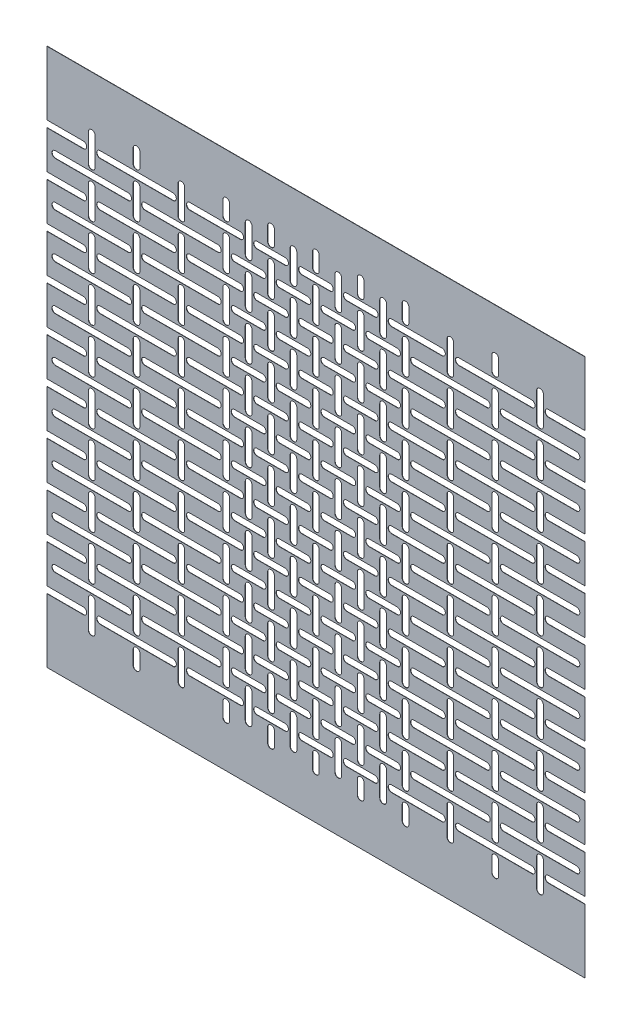
SolidWorks part; units mm, degrees
ref_plane "Front Plane" through (0, 0, 0) normal (0, 0, 1) x (1, 0, 0)
ref_plane "Top Plane" through (0, 0, 0) normal (0, 1, 0) x (1, 0, 0)
ref_plane "Right Plane" through (0, 0, 0) normal (1, 0, 0) x (0, 0, -1)
sketch "Model" plane through (0, 0, 0) normal (0, 0, 1) x (1, 0, 0)
  line L0 (0, 31.5) -> (16.25, 31.5)
  line L1 (0, 28.5) -> (16.25, 28.5)
  line L2 (23.75, 31.5) -> (56.25, 31.5)
  line L3 (23.75, 28.5) -> (56.25, 28.5)
  line L4 (63.75, 31.5) -> (80, 31.5)
  line L5 (63.75, 28.5) -> (80, 28.5)
  line L6 (3.75, 41.5) -> (36.25, 41.5)
  line L7 (3.75, 38.5) -> (36.25, 38.5)
  line L8 (43.75, 41.5) -> (76.25, 41.5)
  line L9 (43.75, 38.5) -> (76.25, 38.5)
  line L10 (0, 51.5) -> (16.25, 51.5)
  line L11 (0, 48.5) -> (16.25, 48.5)
  line L12 (23.75, 51.5) -> (56.25, 51.5)
  line L13 (23.75, 48.5) -> (56.25, 48.5)
  line L14 (63.75, 51.5) -> (80, 51.5)
  line L15 (63.75, 48.5) -> (80, 48.5)
  line L16 (3.75, 61.5) -> (36.25, 61.5)
  line L17 (3.75, 58.5) -> (36.25, 58.5)
  line L18 (43.75, 61.5) -> (76.25, 61.5)
  line L19 (43.75, 58.5) -> (76.25, 58.5)
  line L20 (0, 71.5) -> (16.25, 71.5)
  line L21 (0, 68.5) -> (16.25, 68.5)
  line L22 (23.75, 71.5) -> (56.25, 71.5)
  line L23 (23.75, 68.5) -> (56.25, 68.5)
  line L24 (63.75, 71.5) -> (80, 71.5)
  line L25 (63.75, 68.5) -> (80, 68.5)
  line L26 (3.75, 81.5) -> (36.25, 81.5)
  line L27 (3.75, 78.5) -> (36.25, 78.5)
  line L28 (43.75, 81.5) -> (76.25, 81.5)
  line L29 (43.75, 78.5) -> (76.25, 78.5)
  line L30 (0, 91.5) -> (16.25, 91.5)
  line L31 (0, 88.5) -> (16.25, 88.5)
  line L32 (23.75, 91.5) -> (56.25, 91.5)
  line L33 (23.75, 88.5) -> (56.25, 88.5)
  line L34 (63.75, 91.5) -> (80, 91.5)
  line L35 (63.75, 88.5) -> (80, 88.5)
  line L36 (3.75, 101.5) -> (36.25, 101.5)
  line L37 (3.75, 98.5) -> (36.25, 98.5)
  line L38 (43.75, 101.5) -> (76.25, 101.5)
  line L39 (43.75, 98.5) -> (76.25, 98.5)
  line L40 (0, 111.5) -> (16.25, 111.5)
  line L41 (0, 108.5) -> (16.25, 108.5)
  line L42 (23.75, 111.5) -> (56.25, 111.5)
  line L43 (23.75, 108.5) -> (56.25, 108.5)
  line L44 (63.75, 111.5) -> (80, 111.5)
  line L45 (63.75, 108.5) -> (80, 108.5)
  line L46 (3.75, 121.5) -> (36.25, 121.5)
  line L47 (3.75, 118.5) -> (36.25, 118.5)
  line L48 (43.75, 121.5) -> (76.25, 121.5)
  line L49 (43.75, 118.5) -> (76.25, 118.5)
  line L50 (0, 131.5) -> (16.25, 131.5)
  line L51 (0, 128.5) -> (16.25, 128.5)
  line L52 (23.75, 131.5) -> (56.25, 131.5)
  line L53 (23.75, 128.5) -> (56.25, 128.5)
  line L54 (63.75, 131.5) -> (80, 131.5)
  line L55 (63.75, 128.5) -> (80, 128.5)
  line L56 (3.75, 141.5) -> (36.25, 141.5)
  line L57 (3.75, 138.5) -> (36.25, 138.5)
  line L58 (43.75, 141.5) -> (76.25, 141.5)
  line L59 (43.75, 138.5) -> (76.25, 138.5)
  line L60 (0, 151.5) -> (16.25, 151.5)
  line L61 (0, 148.5) -> (16.25, 148.5)
  line L62 (23.75, 151.5) -> (56.25, 151.5)
  line L63 (23.75, 148.5) -> (56.25, 148.5)
  line L64 (63.75, 151.5) -> (80, 151.5)
  line L65 (63.75, 148.5) -> (80, 148.5)
  line L66 (3.75, 161.5) -> (36.25, 161.5)
  line L67 (3.75, 158.5) -> (36.25, 158.5)
  line L68 (43.75, 161.5) -> (76.25, 161.5)
  line L69 (43.75, 158.5) -> (76.25, 158.5)
  line L70 (0, 171.5) -> (16.25, 171.5)
  line L71 (0, 168.5) -> (16.25, 168.5)
  line L72 (23.75, 171.5) -> (56.25, 171.5)
  line L73 (23.75, 168.5) -> (56.25, 168.5)
  line L74 (63.75, 171.5) -> (80, 171.5)
  line L75 (63.75, 168.5) -> (80, 168.5)
  line L76 (3.75, 181.5) -> (36.25, 181.5)
  line L77 (3.75, 178.5) -> (36.25, 178.5)
  line L78 (43.75, 181.5) -> (76.25, 181.5)
  line L79 (43.75, 178.5) -> (76.25, 178.5)
  line L80 (0, 191.5) -> (16.25, 191.5)
  line L81 (0, 188.5) -> (16.25, 188.5)
  line L82 (23.75, 191.5) -> (56.25, 191.5)
  line L83 (23.75, 188.5) -> (56.25, 188.5)
  line L84 (63.75, 191.5) -> (80, 191.5)
  line L85 (63.75, 188.5) -> (80, 188.5)
  line L86 (3.75, 201.5) -> (36.25, 201.5)
  line L87 (3.75, 198.5) -> (36.25, 198.5)
  line L88 (43.75, 201.5) -> (76.25, 201.5)
  line L89 (43.75, 198.5) -> (76.25, 198.5)
  line L90 (0, 211.5) -> (16.25, 211.5)
  line L91 (0, 208.5) -> (16.25, 208.5)
  line L92 (23.75, 211.5) -> (56.25, 211.5)
  line L93 (23.75, 208.5) -> (56.25, 208.5)
  line L94 (63.75, 211.5) -> (80, 211.5)
  line L95 (63.75, 208.5) -> (80, 208.5)
  line L96 (21.5, 23.75) -> (21.5, 36.25)
  line L97 (18.5, 23.75) -> (18.5, 36.25)
  line L98 (21.5, 43.75) -> (21.5, 56.25)
  line L99 (18.5, 43.75) -> (18.5, 56.25)
  line L100 (21.5, 63.75) -> (21.5, 76.25)
  line L101 (18.5, 63.75) -> (18.5, 76.25)
  line L102 (21.5, 83.75) -> (21.5, 96.25)
  line L103 (18.5, 83.75) -> (18.5, 96.25)
  line L104 (21.5, 103.75) -> (21.5, 116.25)
  line L105 (18.5, 103.75) -> (18.5, 116.25)
  line L106 (21.5, 123.75) -> (21.5, 136.25)
  line L107 (18.5, 123.75) -> (18.5, 136.25)
  line L108 (21.5, 143.75) -> (21.5, 156.25)
  line L109 (18.5, 143.75) -> (18.5, 156.25)
  line L110 (21.5, 163.75) -> (21.5, 176.25)
  line L111 (18.5, 163.75) -> (18.5, 176.25)
  line L112 (21.5, 183.75) -> (21.5, 196.25)
  line L113 (18.5, 183.75) -> (18.5, 196.25)
  line L114 (21.5, 203.75) -> (21.5, 216.25)
  line L115 (18.5, 203.75) -> (18.5, 216.25)
  line L116 (41.5, 20) -> (41.5, 26.25)
  line L117 (38.5, 20) -> (38.5, 26.25)
  line L118 (41.5, 33.75) -> (41.5, 46.25)
  line L119 (38.5, 33.75) -> (38.5, 46.25)
  line L120 (41.5, 53.75) -> (41.5, 66.25)
  line L121 (38.5, 53.75) -> (38.5, 66.25)
  line L122 (41.5, 73.75) -> (41.5, 86.25)
  line L123 (38.5, 73.75) -> (38.5, 86.25)
  line L124 (41.5, 93.75) -> (41.5, 106.25)
  line L125 (38.5, 93.75) -> (38.5, 106.25)
  line L126 (41.5, 113.75) -> (41.5, 126.25)
  line L127 (38.5, 113.75) -> (38.5, 126.25)
  line L128 (41.5, 133.75) -> (41.5, 146.25)
  line L129 (38.5, 133.75) -> (38.5, 146.25)
  line L130 (41.5, 153.75) -> (41.5, 166.25)
  line L131 (38.5, 153.75) -> (38.5, 166.25)
  line L132 (41.5, 173.75) -> (41.5, 186.25)
  line L133 (38.5, 173.75) -> (38.5, 186.25)
  line L134 (41.5, 193.75) -> (41.5, 206.25)
  line L135 (38.5, 193.75) -> (38.5, 206.25)
  line L136 (41.5, 213.75) -> (41.5, 220)
  line L137 (38.5, 213.75) -> (38.5, 220)
  line L138 (61.5, 23.75) -> (61.5, 36.25)
  line L139 (58.5, 23.75) -> (58.5, 36.25)
  line L140 (61.5, 43.75) -> (61.5, 56.25)
  line L141 (58.5, 43.75) -> (58.5, 56.25)
  line L142 (61.5, 63.75) -> (61.5, 76.25)
  line L143 (58.5, 63.75) -> (58.5, 76.25)
  line L144 (61.5, 83.75) -> (61.5, 96.25)
  line L145 (58.5, 83.75) -> (58.5, 96.25)
  line L146 (61.5, 103.75) -> (61.5, 116.25)
  line L147 (58.5, 103.75) -> (58.5, 116.25)
  line L148 (61.5, 123.75) -> (61.5, 136.25)
  line L149 (58.5, 123.75) -> (58.5, 136.25)
  line L150 (61.5, 143.75) -> (61.5, 156.25)
  line L151 (58.5, 143.75) -> (58.5, 156.25)
  line L152 (61.5, 163.75) -> (61.5, 176.25)
  line L153 (58.5, 163.75) -> (58.5, 176.25)
  line L154 (61.5, 183.75) -> (61.5, 196.25)
  line L155 (58.5, 183.75) -> (58.5, 196.25)
  line L156 (61.5, 203.75) -> (61.5, 216.25)
  line L157 (58.5, 203.75) -> (58.5, 216.25)
  line L158 (81.5, 20) -> (81.5, 26.25)
  line L159 (78.5, 20) -> (78.5, 26.25)
  line L160 (81.5, 33.75) -> (81.5, 46.25)
  line L161 (78.5, 33.75) -> (78.5, 46.25)
  line L162 (81.5, 53.75) -> (81.5, 66.25)
  line L163 (78.5, 53.75) -> (78.5, 66.25)
  line L164 (81.5, 73.75) -> (81.5, 86.25)
  line L165 (78.5, 73.75) -> (78.5, 86.25)
  line L166 (81.5, 93.75) -> (81.5, 106.25)
  line L167 (78.5, 93.75) -> (78.5, 106.25)
  line L168 (81.5, 113.75) -> (81.5, 126.25)
  line L169 (78.5, 113.75) -> (78.5, 126.25)
  line L170 (81.5, 133.75) -> (81.5, 146.25)
  line L171 (78.5, 133.75) -> (78.5, 146.25)
  line L172 (81.5, 153.75) -> (81.5, 166.25)
  line L173 (78.5, 153.75) -> (78.5, 166.25)
  line L174 (81.5, 173.75) -> (81.5, 186.25)
  line L175 (78.5, 173.75) -> (78.5, 186.25)
  line L176 (81.5, 193.75) -> (81.5, 206.25)
  line L177 (78.5, 193.75) -> (78.5, 206.25)
  line L178 (81.5, 213.75) -> (81.5, 220)
  line L179 (78.5, 213.75) -> (78.5, 220)
  line L180 (0, 0) -> (80, 0)
  line L181 (80, 240) -> (0, 240)
  line L182 (0, 0) -> (0, 28.5)
  line L183 (0, 31.5) -> (0, 48.5)
  line L184 (0, 51.5) -> (0, 68.5)
  line L185 (0, 71.5) -> (0, 88.5)
  line L186 (0, 91.5) -> (0, 108.5)
  line L187 (0, 111.5) -> (0, 128.5)
  line L188 (0, 131.5) -> (0, 148.5)
  line L189 (0, 151.5) -> (0, 168.5)
  line L190 (0, 171.5) -> (0, 188.5)
  line L191 (0, 191.5) -> (0, 208.5)
  line L192 (0, 211.5) -> (0, 240)
  line L193 (80, 31.5) -> (86.25, 31.5)
  line L194 (80, 28.5) -> (86.25, 28.5)
  line L195 (93.75, 31.5) -> (106.25, 31.5)
  line L196 (93.75, 28.5) -> (106.25, 28.5)
  line L197 (113.75, 31.5) -> (126.25, 31.5)
  line L198 (113.75, 28.5) -> (126.25, 28.5)
  line L199 (133.75, 31.5) -> (146.25, 31.5)
  line L200 (133.75, 28.5) -> (146.25, 28.5)
  line L201 (153.75, 31.5) -> (160, 31.5)
  line L202 (153.75, 28.5) -> (160, 28.5)
  line L203 (83.75, 41.5) -> (96.25, 41.5)
  line L204 (83.75, 38.5) -> (96.25, 38.5)
  line L205 (103.75, 41.5) -> (116.25, 41.5)
  line L206 (103.75, 38.5) -> (116.25, 38.5)
  line L207 (123.75, 41.5) -> (136.25, 41.5)
  line L208 (123.75, 38.5) -> (136.25, 38.5)
  line L209 (143.75, 41.5) -> (156.25, 41.5)
  line L210 (143.75, 38.5) -> (156.25, 38.5)
  line L211 (80, 51.5) -> (86.25, 51.5)
  line L212 (80, 48.5) -> (86.25, 48.5)
  line L213 (93.75, 51.5) -> (106.25, 51.5)
  line L214 (93.75, 48.5) -> (106.25, 48.5)
  line L215 (113.75, 51.5) -> (126.25, 51.5)
  line L216 (113.75, 48.5) -> (126.25, 48.5)
  line L217 (133.75, 51.5) -> (146.25, 51.5)
  line L218 (133.75, 48.5) -> (146.25, 48.5)
  line L219 (153.75, 51.5) -> (160, 51.5)
  line L220 (153.75, 48.5) -> (160, 48.5)
  line L221 (83.75, 61.5) -> (96.25, 61.5)
  line L222 (83.75, 58.5) -> (96.25, 58.5)
  line L223 (103.75, 61.5) -> (116.25, 61.5)
  line L224 (103.75, 58.5) -> (116.25, 58.5)
  line L225 (123.75, 61.5) -> (136.25, 61.5)
  line L226 (123.75, 58.5) -> (136.25, 58.5)
  line L227 (143.75, 61.5) -> (156.25, 61.5)
  line L228 (143.75, 58.5) -> (156.25, 58.5)
  line L229 (80, 71.5) -> (86.25, 71.5)
  line L230 (80, 68.5) -> (86.25, 68.5)
  line L231 (93.75, 71.5) -> (106.25, 71.5)
  line L232 (93.75, 68.5) -> (106.25, 68.5)
  line L233 (113.75, 71.5) -> (126.25, 71.5)
  line L234 (113.75, 68.5) -> (126.25, 68.5)
  line L235 (133.75, 71.5) -> (146.25, 71.5)
  line L236 (133.75, 68.5) -> (146.25, 68.5)
  line L237 (153.75, 71.5) -> (160, 71.5)
  line L238 (153.75, 68.5) -> (160, 68.5)
  line L239 (83.75, 81.5) -> (96.25, 81.5)
  line L240 (83.75, 78.5) -> (96.25, 78.5)
  line L241 (103.75, 81.5) -> (116.25, 81.5)
  line L242 (103.75, 78.5) -> (116.25, 78.5)
  line L243 (123.75, 81.5) -> (136.25, 81.5)
  line L244 (123.75, 78.5) -> (136.25, 78.5)
  line L245 (143.75, 81.5) -> (156.25, 81.5)
  line L246 (143.75, 78.5) -> (156.25, 78.5)
  line L247 (80, 91.5) -> (86.25, 91.5)
  line L248 (80, 88.5) -> (86.25, 88.5)
  line L249 (93.75, 91.5) -> (106.25, 91.5)
  line L250 (93.75, 88.5) -> (106.25, 88.5)
  line L251 (113.75, 91.5) -> (126.25, 91.5)
  line L252 (113.75, 88.5) -> (126.25, 88.5)
  line L253 (133.75, 91.5) -> (146.25, 91.5)
  line L254 (133.75, 88.5) -> (146.25, 88.5)
  line L255 (153.75, 91.5) -> (160, 91.5)
  line L256 (153.75, 88.5) -> (160, 88.5)
  line L257 (83.75, 101.5) -> (96.25, 101.5)
  line L258 (83.75, 98.5) -> (96.25, 98.5)
  line L259 (103.75, 101.5) -> (116.25, 101.5)
  line L260 (103.75, 98.5) -> (116.25, 98.5)
  line L261 (123.75, 101.5) -> (136.25, 101.5)
  line L262 (123.75, 98.5) -> (136.25, 98.5)
  line L263 (143.75, 101.5) -> (156.25, 101.5)
  line L264 (143.75, 98.5) -> (156.25, 98.5)
  line L265 (80, 111.5) -> (86.25, 111.5)
  line L266 (80, 108.5) -> (86.25, 108.5)
  line L267 (93.75, 111.5) -> (106.25, 111.5)
  line L268 (93.75, 108.5) -> (106.25, 108.5)
  line L269 (113.75, 111.5) -> (126.25, 111.5)
  line L270 (113.75, 108.5) -> (126.25, 108.5)
  line L271 (133.75, 111.5) -> (146.25, 111.5)
  line L272 (133.75, 108.5) -> (146.25, 108.5)
  line L273 (153.75, 111.5) -> (160, 111.5)
  line L274 (153.75, 108.5) -> (160, 108.5)
  line L275 (83.75, 121.5) -> (96.25, 121.5)
  line L276 (83.75, 118.5) -> (96.25, 118.5)
  line L277 (103.75, 121.5) -> (116.25, 121.5)
  line L278 (103.75, 118.5) -> (116.25, 118.5)
  line L279 (123.75, 121.5) -> (136.25, 121.5)
  line L280 (123.75, 118.5) -> (136.25, 118.5)
  line L281 (143.75, 121.5) -> (156.25, 121.5)
  line L282 (143.75, 118.5) -> (156.25, 118.5)
  line L283 (80, 131.5) -> (86.25, 131.5)
  line L284 (80, 128.5) -> (86.25, 128.5)
  line L285 (93.75, 131.5) -> (106.25, 131.5)
  line L286 (93.75, 128.5) -> (106.25, 128.5)
  line L287 (113.75, 131.5) -> (126.25, 131.5)
  line L288 (113.75, 128.5) -> (126.25, 128.5)
  line L289 (133.75, 131.5) -> (146.25, 131.5)
  line L290 (133.75, 128.5) -> (146.25, 128.5)
  line L291 (153.75, 131.5) -> (160, 131.5)
  line L292 (153.75, 128.5) -> (160, 128.5)
  line L293 (83.75, 141.5) -> (96.25, 141.5)
  line L294 (83.75, 138.5) -> (96.25, 138.5)
  line L295 (103.75, 141.5) -> (116.25, 141.5)
  line L296 (103.75, 138.5) -> (116.25, 138.5)
  line L297 (123.75, 141.5) -> (136.25, 141.5)
  line L298 (123.75, 138.5) -> (136.25, 138.5)
  line L299 (143.75, 141.5) -> (156.25, 141.5)
  line L300 (143.75, 138.5) -> (156.25, 138.5)
  line L301 (80, 151.5) -> (86.25, 151.5)
  line L302 (80, 148.5) -> (86.25, 148.5)
  line L303 (93.75, 151.5) -> (106.25, 151.5)
  line L304 (93.75, 148.5) -> (106.25, 148.5)
  line L305 (113.75, 151.5) -> (126.25, 151.5)
  line L306 (113.75, 148.5) -> (126.25, 148.5)
  line L307 (133.75, 151.5) -> (146.25, 151.5)
  line L308 (133.75, 148.5) -> (146.25, 148.5)
  line L309 (153.75, 151.5) -> (160, 151.5)
  line L310 (153.75, 148.5) -> (160, 148.5)
  line L311 (83.75, 161.5) -> (96.25, 161.5)
  line L312 (83.75, 158.5) -> (96.25, 158.5)
  line L313 (103.75, 161.5) -> (116.25, 161.5)
  line L314 (103.75, 158.5) -> (116.25, 158.5)
  line L315 (123.75, 161.5) -> (136.25, 161.5)
  line L316 (123.75, 158.5) -> (136.25, 158.5)
  line L317 (143.75, 161.5) -> (156.25, 161.5)
  line L318 (143.75, 158.5) -> (156.25, 158.5)
  line L319 (80, 171.5) -> (86.25, 171.5)
  line L320 (80, 168.5) -> (86.25, 168.5)
  line L321 (93.75, 171.5) -> (106.25, 171.5)
  line L322 (93.75, 168.5) -> (106.25, 168.5)
  line L323 (113.75, 171.5) -> (126.25, 171.5)
  line L324 (113.75, 168.5) -> (126.25, 168.5)
  line L325 (133.75, 171.5) -> (146.25, 171.5)
  line L326 (133.75, 168.5) -> (146.25, 168.5)
  line L327 (153.75, 171.5) -> (160, 171.5)
  line L328 (153.75, 168.5) -> (160, 168.5)
  line L329 (83.75, 181.5) -> (96.25, 181.5)
  line L330 (83.75, 178.5) -> (96.25, 178.5)
  line L331 (103.75, 181.5) -> (116.25, 181.5)
  line L332 (103.75, 178.5) -> (116.25, 178.5)
  line L333 (123.75, 181.5) -> (136.25, 181.5)
  line L334 (123.75, 178.5) -> (136.25, 178.5)
  line L335 (143.75, 181.5) -> (156.25, 181.5)
  line L336 (143.75, 178.5) -> (156.25, 178.5)
  line L337 (80, 191.5) -> (86.25, 191.5)
  line L338 (80, 188.5) -> (86.25, 188.5)
  line L339 (93.75, 191.5) -> (106.25, 191.5)
  line L340 (93.75, 188.5) -> (106.25, 188.5)
  line L341 (113.75, 191.5) -> (126.25, 191.5)
  line L342 (113.75, 188.5) -> (126.25, 188.5)
  line L343 (133.75, 191.5) -> (146.25, 191.5)
  line L344 (133.75, 188.5) -> (146.25, 188.5)
  line L345 (153.75, 191.5) -> (160, 191.5)
  line L346 (153.75, 188.5) -> (160, 188.5)
  line L347 (83.75, 201.5) -> (96.25, 201.5)
  line L348 (83.75, 198.5) -> (96.25, 198.5)
  line L349 (103.75, 201.5) -> (116.25, 201.5)
  line L350 (103.75, 198.5) -> (116.25, 198.5)
  line L351 (123.75, 201.5) -> (136.25, 201.5)
  line L352 (123.75, 198.5) -> (136.25, 198.5)
  line L353 (143.75, 201.5) -> (156.25, 201.5)
  line L354 (143.75, 198.5) -> (156.25, 198.5)
  line L355 (80, 211.5) -> (86.25, 211.5)
  line L356 (80, 208.5) -> (86.25, 208.5)
  line L357 (93.75, 211.5) -> (106.25, 211.5)
  line L358 (93.75, 208.5) -> (106.25, 208.5)
  line L359 (113.75, 211.5) -> (126.25, 211.5)
  line L360 (113.75, 208.5) -> (126.25, 208.5)
  line L361 (133.75, 211.5) -> (146.25, 211.5)
  line L362 (133.75, 208.5) -> (146.25, 208.5)
  line L363 (153.75, 211.5) -> (160, 211.5)
  line L364 (153.75, 208.5) -> (160, 208.5)
  line L365 (91.5, 23.75) -> (91.5, 36.25)
  line L366 (88.5, 23.75) -> (88.5, 36.25)
  line L367 (91.5, 43.75) -> (91.5, 56.25)
  line L368 (88.5, 43.75) -> (88.5, 56.25)
  line L369 (91.5, 63.75) -> (91.5, 76.25)
  line L370 (88.5, 63.75) -> (88.5, 76.25)
  line L371 (91.5, 83.75) -> (91.5, 96.25)
  line L372 (88.5, 83.75) -> (88.5, 96.25)
  line L373 (91.5, 103.75) -> (91.5, 116.25)
  line L374 (88.5, 103.75) -> (88.5, 116.25)
  line L375 (91.5, 123.75) -> (91.5, 136.25)
  line L376 (88.5, 123.75) -> (88.5, 136.25)
  line L377 (91.5, 143.75) -> (91.5, 156.25)
  line L378 (88.5, 143.75) -> (88.5, 156.25)
  line L379 (91.5, 163.75) -> (91.5, 176.25)
  line L380 (88.5, 163.75) -> (88.5, 176.25)
  line L381 (91.5, 183.75) -> (91.5, 196.25)
  line L382 (88.5, 183.75) -> (88.5, 196.25)
  line L383 (91.5, 203.75) -> (91.5, 216.25)
  line L384 (88.5, 203.75) -> (88.5, 216.25)
  line L385 (101.5, 20) -> (101.5, 26.25)
  line L386 (98.5, 20) -> (98.5, 26.25)
  line L387 (101.5, 33.75) -> (101.5, 46.25)
  line L388 (98.5, 33.75) -> (98.5, 46.25)
  line L389 (101.5, 53.75) -> (101.5, 66.25)
  line L390 (98.5, 53.75) -> (98.5, 66.25)
  line L391 (101.5, 73.75) -> (101.5, 86.25)
  line L392 (98.5, 73.75) -> (98.5, 86.25)
  line L393 (101.5, 93.75) -> (101.5, 106.25)
  line L394 (98.5, 93.75) -> (98.5, 106.25)
  line L395 (101.5, 113.75) -> (101.5, 126.25)
  line L396 (98.5, 113.75) -> (98.5, 126.25)
  line L397 (101.5, 133.75) -> (101.5, 146.25)
  line L398 (98.5, 133.75) -> (98.5, 146.25)
  line L399 (101.5, 153.75) -> (101.5, 166.25)
  line L400 (98.5, 153.75) -> (98.5, 166.25)
  line L401 (101.5, 173.75) -> (101.5, 186.25)
  line L402 (98.5, 173.75) -> (98.5, 186.25)
  line L403 (101.5, 193.75) -> (101.5, 206.25)
  line L404 (98.5, 193.75) -> (98.5, 206.25)
  line L405 (101.5, 213.75) -> (101.5, 220)
  line L406 (98.5, 213.75) -> (98.5, 220)
  line L407 (111.5, 23.75) -> (111.5, 36.25)
  line L408 (108.5, 23.75) -> (108.5, 36.25)
  line L409 (111.5, 43.75) -> (111.5, 56.25)
  line L410 (108.5, 43.75) -> (108.5, 56.25)
  line L411 (111.5, 63.75) -> (111.5, 76.25)
  line L412 (108.5, 63.75) -> (108.5, 76.25)
  line L413 (111.5, 83.75) -> (111.5, 96.25)
  line L414 (108.5, 83.75) -> (108.5, 96.25)
  line L415 (111.5, 103.75) -> (111.5, 116.25)
  line L416 (108.5, 103.75) -> (108.5, 116.25)
  line L417 (111.5, 123.75) -> (111.5, 136.25)
  line L418 (108.5, 123.75) -> (108.5, 136.25)
  line L419 (111.5, 143.75) -> (111.5, 156.25)
  line L420 (108.5, 143.75) -> (108.5, 156.25)
  line L421 (111.5, 163.75) -> (111.5, 176.25)
  line L422 (108.5, 163.75) -> (108.5, 176.25)
  line L423 (111.5, 183.75) -> (111.5, 196.25)
  line L424 (108.5, 183.75) -> (108.5, 196.25)
  line L425 (111.5, 203.75) -> (111.5, 216.25)
  line L426 (108.5, 203.75) -> (108.5, 216.25)
  line L427 (121.5, 20) -> (121.5, 26.25)
  line L428 (118.5, 20) -> (118.5, 26.25)
  line L429 (121.5, 33.75) -> (121.5, 46.25)
  line L430 (118.5, 33.75) -> (118.5, 46.25)
  line L431 (121.5, 53.75) -> (121.5, 66.25)
  line L432 (118.5, 53.75) -> (118.5, 66.25)
  line L433 (121.5, 73.75) -> (121.5, 86.25)
  line L434 (118.5, 73.75) -> (118.5, 86.25)
  line L435 (121.5, 93.75) -> (121.5, 106.25)
  line L436 (118.5, 93.75) -> (118.5, 106.25)
  line L437 (121.5, 113.75) -> (121.5, 126.25)
  line L438 (118.5, 113.75) -> (118.5, 126.25)
  line L439 (121.5, 133.75) -> (121.5, 146.25)
  line L440 (118.5, 133.75) -> (118.5, 146.25)
  line L441 (121.5, 153.75) -> (121.5, 166.25)
  line L442 (118.5, 153.75) -> (118.5, 166.25)
  line L443 (121.5, 173.75) -> (121.5, 186.25)
  line L444 (118.5, 173.75) -> (118.5, 186.25)
  line L445 (121.5, 193.75) -> (121.5, 206.25)
  line L446 (118.5, 193.75) -> (118.5, 206.25)
  line L447 (121.5, 213.75) -> (121.5, 220)
  line L448 (118.5, 213.75) -> (118.5, 220)
  line L449 (131.5, 23.75) -> (131.5, 36.25)
  line L450 (128.5, 23.75) -> (128.5, 36.25)
  line L451 (131.5, 43.75) -> (131.5, 56.25)
  line L452 (128.5, 43.75) -> (128.5, 56.25)
  line L453 (131.5, 63.75) -> (131.5, 76.25)
  line L454 (128.5, 63.75) -> (128.5, 76.25)
  line L455 (131.5, 83.75) -> (131.5, 96.25)
  line L456 (128.5, 83.75) -> (128.5, 96.25)
  line L457 (131.5, 103.75) -> (131.5, 116.25)
  line L458 (128.5, 103.75) -> (128.5, 116.25)
  line L459 (131.5, 123.75) -> (131.5, 136.25)
  line L460 (128.5, 123.75) -> (128.5, 136.25)
  line L461 (131.5, 143.75) -> (131.5, 156.25)
  line L462 (128.5, 143.75) -> (128.5, 156.25)
  line L463 (131.5, 163.75) -> (131.5, 176.25)
  line L464 (128.5, 163.75) -> (128.5, 176.25)
  line L465 (131.5, 183.75) -> (131.5, 196.25)
  line L466 (128.5, 183.75) -> (128.5, 196.25)
  line L467 (131.5, 203.75) -> (131.5, 216.25)
  line L468 (128.5, 203.75) -> (128.5, 216.25)
  line L469 (141.5, 20) -> (141.5, 26.25)
  line L470 (138.5, 20) -> (138.5, 26.25)
  line L471 (141.5, 33.75) -> (141.5, 46.25)
  line L472 (138.5, 33.75) -> (138.5, 46.25)
  line L473 (141.5, 53.75) -> (141.5, 66.25)
  line L474 (138.5, 53.75) -> (138.5, 66.25)
  line L475 (141.5, 73.75) -> (141.5, 86.25)
  line L476 (138.5, 73.75) -> (138.5, 86.25)
  line L477 (141.5, 93.75) -> (141.5, 106.25)
  line L478 (138.5, 93.75) -> (138.5, 106.25)
  line L479 (141.5, 113.75) -> (141.5, 126.25)
  line L480 (138.5, 113.75) -> (138.5, 126.25)
  line L481 (141.5, 133.75) -> (141.5, 146.25)
  line L482 (138.5, 133.75) -> (138.5, 146.25)
  line L483 (141.5, 153.75) -> (141.5, 166.25)
  line L484 (138.5, 153.75) -> (138.5, 166.25)
  line L485 (141.5, 173.75) -> (141.5, 186.25)
  line L486 (138.5, 173.75) -> (138.5, 186.25)
  line L487 (141.5, 193.75) -> (141.5, 206.25)
  line L488 (138.5, 193.75) -> (138.5, 206.25)
  line L489 (141.5, 213.75) -> (141.5, 220)
  line L490 (138.5, 213.75) -> (138.5, 220)
  line L491 (151.5, 23.75) -> (151.5, 36.25)
  line L492 (148.5, 23.75) -> (148.5, 36.25)
  line L493 (151.5, 43.75) -> (151.5, 56.25)
  line L494 (148.5, 43.75) -> (148.5, 56.25)
  line L495 (151.5, 63.75) -> (151.5, 76.25)
  line L496 (148.5, 63.75) -> (148.5, 76.25)
  line L497 (151.5, 83.75) -> (151.5, 96.25)
  line L498 (148.5, 83.75) -> (148.5, 96.25)
  line L499 (151.5, 103.75) -> (151.5, 116.25)
  line L500 (148.5, 103.75) -> (148.5, 116.25)
  line L501 (151.5, 123.75) -> (151.5, 136.25)
  line L502 (148.5, 123.75) -> (148.5, 136.25)
  line L503 (151.5, 143.75) -> (151.5, 156.25)
  line L504 (148.5, 143.75) -> (148.5, 156.25)
  line L505 (151.5, 163.75) -> (151.5, 176.25)
  line L506 (148.5, 163.75) -> (148.5, 176.25)
  line L507 (151.5, 183.75) -> (151.5, 196.25)
  line L508 (148.5, 183.75) -> (148.5, 196.25)
  line L509 (151.5, 203.75) -> (151.5, 216.25)
  line L510 (148.5, 203.75) -> (148.5, 216.25)
  line L511 (161.5, 20) -> (161.5, 26.25)
  line L512 (158.5, 20) -> (158.5, 26.25)
  line L513 (161.5, 33.75) -> (161.5, 46.25)
  line L514 (158.5, 33.75) -> (158.5, 46.25)
  line L515 (161.5, 53.75) -> (161.5, 66.25)
  line L516 (158.5, 53.75) -> (158.5, 66.25)
  line L517 (161.5, 73.75) -> (161.5, 86.25)
  line L518 (158.5, 73.75) -> (158.5, 86.25)
  line L519 (161.5, 93.75) -> (161.5, 106.25)
  line L520 (158.5, 93.75) -> (158.5, 106.25)
  line L521 (161.5, 113.75) -> (161.5, 126.25)
  line L522 (158.5, 113.75) -> (158.5, 126.25)
  line L523 (161.5, 133.75) -> (161.5, 146.25)
  line L524 (158.5, 133.75) -> (158.5, 146.25)
  line L525 (161.5, 153.75) -> (161.5, 166.25)
  line L526 (158.5, 153.75) -> (158.5, 166.25)
  line L527 (161.5, 173.75) -> (161.5, 186.25)
  line L528 (158.5, 173.75) -> (158.5, 186.25)
  line L529 (161.5, 193.75) -> (161.5, 206.25)
  line L530 (158.5, 193.75) -> (158.5, 206.25)
  line L531 (161.5, 213.75) -> (161.5, 220)
  line L532 (158.5, 213.75) -> (158.5, 220)
  line L533 (80, 0) -> (160, 0)
  line L534 (160, 240) -> (80, 240)
  line L535 (160, 31.5) -> (176.25, 31.5)
  line L536 (160, 28.5) -> (176.25, 28.5)
  line L537 (183.75, 31.5) -> (216.25, 31.5)
  line L538 (183.75, 28.5) -> (216.25, 28.5)
  line L539 (223.75, 31.5) -> (240, 31.5)
  line L540 (223.75, 28.5) -> (240, 28.5)
  line L541 (163.75, 41.5) -> (196.25, 41.5)
  line L542 (163.75, 38.5) -> (196.25, 38.5)
  line L543 (203.75, 41.5) -> (236.25, 41.5)
  line L544 (203.75, 38.5) -> (236.25, 38.5)
  line L545 (160, 51.5) -> (176.25, 51.5)
  line L546 (160, 48.5) -> (176.25, 48.5)
  line L547 (183.75, 51.5) -> (216.25, 51.5)
  line L548 (183.75, 48.5) -> (216.25, 48.5)
  line L549 (223.75, 51.5) -> (240, 51.5)
  line L550 (223.75, 48.5) -> (240, 48.5)
  line L551 (163.75, 61.5) -> (196.25, 61.5)
  line L552 (163.75, 58.5) -> (196.25, 58.5)
  line L553 (203.75, 61.5) -> (236.25, 61.5)
  line L554 (203.75, 58.5) -> (236.25, 58.5)
  line L555 (160, 71.5) -> (176.25, 71.5)
  line L556 (160, 68.5) -> (176.25, 68.5)
  line L557 (183.75, 71.5) -> (216.25, 71.5)
  line L558 (183.75, 68.5) -> (216.25, 68.5)
  line L559 (223.75, 71.5) -> (240, 71.5)
  line L560 (223.75, 68.5) -> (240, 68.5)
  line L561 (163.75, 81.5) -> (196.25, 81.5)
  line L562 (163.75, 78.5) -> (196.25, 78.5)
  line L563 (203.75, 81.5) -> (236.25, 81.5)
  line L564 (203.75, 78.5) -> (236.25, 78.5)
  line L565 (160, 91.5) -> (176.25, 91.5)
  line L566 (160, 88.5) -> (176.25, 88.5)
  line L567 (183.75, 91.5) -> (216.25, 91.5)
  line L568 (183.75, 88.5) -> (216.25, 88.5)
  line L569 (223.75, 91.5) -> (240, 91.5)
  line L570 (223.75, 88.5) -> (240, 88.5)
  line L571 (163.75, 101.5) -> (196.25, 101.5)
  line L572 (163.75, 98.5) -> (196.25, 98.5)
  line L573 (203.75, 101.5) -> (236.25, 101.5)
  line L574 (203.75, 98.5) -> (236.25, 98.5)
  line L575 (160, 111.5) -> (176.25, 111.5)
  line L576 (160, 108.5) -> (176.25, 108.5)
  line L577 (183.75, 111.5) -> (216.25, 111.5)
  line L578 (183.75, 108.5) -> (216.25, 108.5)
  line L579 (223.75, 111.5) -> (240, 111.5)
  line L580 (223.75, 108.5) -> (240, 108.5)
  line L581 (163.75, 121.5) -> (196.25, 121.5)
  line L582 (163.75, 118.5) -> (196.25, 118.5)
  line L583 (203.75, 121.5) -> (236.25, 121.5)
  line L584 (203.75, 118.5) -> (236.25, 118.5)
  line L585 (160, 131.5) -> (176.25, 131.5)
  line L586 (160, 128.5) -> (176.25, 128.5)
  line L587 (183.75, 131.5) -> (216.25, 131.5)
  line L588 (183.75, 128.5) -> (216.25, 128.5)
  line L589 (223.75, 131.5) -> (240, 131.5)
  line L590 (223.75, 128.5) -> (240, 128.5)
  line L591 (163.75, 141.5) -> (196.25, 141.5)
  line L592 (163.75, 138.5) -> (196.25, 138.5)
  line L593 (203.75, 141.5) -> (236.25, 141.5)
  line L594 (203.75, 138.5) -> (236.25, 138.5)
  line L595 (160, 151.5) -> (176.25, 151.5)
  line L596 (160, 148.5) -> (176.25, 148.5)
  line L597 (183.75, 151.5) -> (216.25, 151.5)
  line L598 (183.75, 148.5) -> (216.25, 148.5)
  line L599 (223.75, 151.5) -> (240, 151.5)
  line L600 (223.75, 148.5) -> (240, 148.5)
  line L601 (163.75, 161.5) -> (196.25, 161.5)
  line L602 (163.75, 158.5) -> (196.25, 158.5)
  line L603 (203.75, 161.5) -> (236.25, 161.5)
  line L604 (203.75, 158.5) -> (236.25, 158.5)
  line L605 (160, 171.5) -> (176.25, 171.5)
  line L606 (160, 168.5) -> (176.25, 168.5)
  line L607 (183.75, 171.5) -> (216.25, 171.5)
  line L608 (183.75, 168.5) -> (216.25, 168.5)
  line L609 (223.75, 171.5) -> (240, 171.5)
  line L610 (223.75, 168.5) -> (240, 168.5)
  line L611 (163.75, 181.5) -> (196.25, 181.5)
  line L612 (163.75, 178.5) -> (196.25, 178.5)
  line L613 (203.75, 181.5) -> (236.25, 181.5)
  line L614 (203.75, 178.5) -> (236.25, 178.5)
  line L615 (160, 191.5) -> (176.25, 191.5)
  line L616 (160, 188.5) -> (176.25, 188.5)
  line L617 (183.75, 191.5) -> (216.25, 191.5)
  line L618 (183.75, 188.5) -> (216.25, 188.5)
  line L619 (223.75, 191.5) -> (240, 191.5)
  line L620 (223.75, 188.5) -> (240, 188.5)
  line L621 (163.75, 201.5) -> (196.25, 201.5)
  line L622 (163.75, 198.5) -> (196.25, 198.5)
  line L623 (203.75, 201.5) -> (236.25, 201.5)
  line L624 (203.75, 198.5) -> (236.25, 198.5)
  line L625 (160, 211.5) -> (176.25, 211.5)
  line L626 (160, 208.5) -> (176.25, 208.5)
  line L627 (183.75, 211.5) -> (216.25, 211.5)
  line L628 (183.75, 208.5) -> (216.25, 208.5)
  line L629 (223.75, 211.5) -> (240, 211.5)
  line L630 (223.75, 208.5) -> (240, 208.5)
  line L631 (181.5, 23.75) -> (181.5, 36.25)
  line L632 (178.5, 23.75) -> (178.5, 36.25)
  line L633 (181.5, 43.75) -> (181.5, 56.25)
  line L634 (178.5, 43.75) -> (178.5, 56.25)
  line L635 (181.5, 63.75) -> (181.5, 76.25)
  line L636 (178.5, 63.75) -> (178.5, 76.25)
  line L637 (181.5, 83.75) -> (181.5, 96.25)
  line L638 (178.5, 83.75) -> (178.5, 96.25)
  line L639 (181.5, 103.75) -> (181.5, 116.25)
  line L640 (178.5, 103.75) -> (178.5, 116.25)
  line L641 (181.5, 123.75) -> (181.5, 136.25)
  line L642 (178.5, 123.75) -> (178.5, 136.25)
  line L643 (181.5, 143.75) -> (181.5, 156.25)
  line L644 (178.5, 143.75) -> (178.5, 156.25)
  line L645 (181.5, 163.75) -> (181.5, 176.25)
  line L646 (178.5, 163.75) -> (178.5, 176.25)
  line L647 (181.5, 183.75) -> (181.5, 196.25)
  line L648 (178.5, 183.75) -> (178.5, 196.25)
  line L649 (181.5, 203.75) -> (181.5, 216.25)
  line L650 (178.5, 203.75) -> (178.5, 216.25)
  line L651 (201.5, 20) -> (201.5, 26.25)
  line L652 (198.5, 20) -> (198.5, 26.25)
  line L653 (201.5, 33.75) -> (201.5, 46.25)
  line L654 (198.5, 33.75) -> (198.5, 46.25)
  line L655 (201.5, 53.75) -> (201.5, 66.25)
  line L656 (198.5, 53.75) -> (198.5, 66.25)
  line L657 (201.5, 73.75) -> (201.5, 86.25)
  line L658 (198.5, 73.75) -> (198.5, 86.25)
  line L659 (201.5, 93.75) -> (201.5, 106.25)
  line L660 (198.5, 93.75) -> (198.5, 106.25)
  line L661 (201.5, 113.75) -> (201.5, 126.25)
  line L662 (198.5, 113.75) -> (198.5, 126.25)
  line L663 (201.5, 133.75) -> (201.5, 146.25)
  line L664 (198.5, 133.75) -> (198.5, 146.25)
  line L665 (201.5, 153.75) -> (201.5, 166.25)
  line L666 (198.5, 153.75) -> (198.5, 166.25)
  line L667 (201.5, 173.75) -> (201.5, 186.25)
  line L668 (198.5, 173.75) -> (198.5, 186.25)
  line L669 (201.5, 193.75) -> (201.5, 206.25)
  line L670 (198.5, 193.75) -> (198.5, 206.25)
  line L671 (201.5, 213.75) -> (201.5, 220)
  line L672 (198.5, 213.75) -> (198.5, 220)
  line L673 (221.5, 23.75) -> (221.5, 36.25)
  line L674 (218.5, 23.75) -> (218.5, 36.25)
  line L675 (221.5, 43.75) -> (221.5, 56.25)
  line L676 (218.5, 43.75) -> (218.5, 56.25)
  line L677 (221.5, 63.75) -> (221.5, 76.25)
  line L678 (218.5, 63.75) -> (218.5, 76.25)
  line L679 (221.5, 83.75) -> (221.5, 96.25)
  line L680 (218.5, 83.75) -> (218.5, 96.25)
  line L681 (221.5, 103.75) -> (221.5, 116.25)
  line L682 (218.5, 103.75) -> (218.5, 116.25)
  line L683 (221.5, 123.75) -> (221.5, 136.25)
  line L684 (218.5, 123.75) -> (218.5, 136.25)
  line L685 (221.5, 143.75) -> (221.5, 156.25)
  line L686 (218.5, 143.75) -> (218.5, 156.25)
  line L687 (221.5, 163.75) -> (221.5, 176.25)
  line L688 (218.5, 163.75) -> (218.5, 176.25)
  line L689 (221.5, 183.75) -> (221.5, 196.25)
  line L690 (218.5, 183.75) -> (218.5, 196.25)
  line L691 (221.5, 203.75) -> (221.5, 216.25)
  line L692 (218.5, 203.75) -> (218.5, 216.25)
  line L693 (160, 0) -> (240, 0)
  line L694 (240, 0) -> (240, 28.5)
  line L695 (240, 31.5) -> (240, 48.5)
  line L696 (240, 51.5) -> (240, 68.5)
  line L697 (240, 71.5) -> (240, 88.5)
  line L698 (240, 91.5) -> (240, 108.5)
  line L699 (240, 111.5) -> (240, 128.5)
  line L700 (240, 131.5) -> (240, 148.5)
  line L701 (240, 151.5) -> (240, 168.5)
  line L702 (240, 171.5) -> (240, 188.5)
  line L703 (240, 191.5) -> (240, 208.5)
  line L704 (240, 211.5) -> (240, 240)
  line L705 (240, 240) -> (160, 240)
  arc A0 (16.25, 28.5) -> (16.25, 31.5) centre (16.25, 30) ccw
  arc A1 (23.75, 31.5) -> (23.75, 28.5) centre (23.75, 30) ccw
  arc A2 (56.25, 28.5) -> (56.25, 31.5) centre (56.25, 30) ccw
  arc A3 (63.75, 31.5) -> (63.75, 28.5) centre (63.75, 30) ccw
  arc A4 (3.75, 41.5) -> (3.75, 38.5) centre (3.75, 40) ccw
  arc A5 (36.25, 38.5) -> (36.25, 41.5) centre (36.25, 40) ccw
  arc A6 (43.75, 41.5) -> (43.75, 38.5) centre (43.75, 40) ccw
  arc A7 (76.25, 38.5) -> (76.25, 41.5) centre (76.25, 40) ccw
  arc A8 (16.25, 48.5) -> (16.25, 51.5) centre (16.25, 50) ccw
  arc A9 (23.75, 51.5) -> (23.75, 48.5) centre (23.75, 50) ccw
  arc A10 (56.25, 48.5) -> (56.25, 51.5) centre (56.25, 50) ccw
  arc A11 (63.75, 51.5) -> (63.75, 48.5) centre (63.75, 50) ccw
  arc A12 (3.75, 61.5) -> (3.75, 58.5) centre (3.75, 60) ccw
  arc A13 (36.25, 58.5) -> (36.25, 61.5) centre (36.25, 60) ccw
  arc A14 (43.75, 61.5) -> (43.75, 58.5) centre (43.75, 60) ccw
  arc A15 (76.25, 58.5) -> (76.25, 61.5) centre (76.25, 60) ccw
  arc A16 (16.25, 68.5) -> (16.25, 71.5) centre (16.25, 70) ccw
  arc A17 (23.75, 71.5) -> (23.75, 68.5) centre (23.75, 70) ccw
  arc A18 (56.25, 68.5) -> (56.25, 71.5) centre (56.25, 70) ccw
  arc A19 (63.75, 71.5) -> (63.75, 68.5) centre (63.75, 70) ccw
  arc A20 (3.75, 81.5) -> (3.75, 78.5) centre (3.75, 80) ccw
  arc A21 (36.25, 78.5) -> (36.25, 81.5) centre (36.25, 80) ccw
  arc A22 (43.75, 81.5) -> (43.75, 78.5) centre (43.75, 80) ccw
  arc A23 (76.25, 78.5) -> (76.25, 81.5) centre (76.25, 80) ccw
  arc A24 (16.25, 88.5) -> (16.25, 91.5) centre (16.25, 90) ccw
  arc A25 (23.75, 91.5) -> (23.75, 88.5) centre (23.75, 90) ccw
  arc A26 (56.25, 88.5) -> (56.25, 91.5) centre (56.25, 90) ccw
  arc A27 (63.75, 91.5) -> (63.75, 88.5) centre (63.75, 90) ccw
  arc A28 (3.75, 101.5) -> (3.75, 98.5) centre (3.75, 100) ccw
  arc A29 (36.25, 98.5) -> (36.25, 101.5) centre (36.25, 100) ccw
  arc A30 (43.75, 101.5) -> (43.75, 98.5) centre (43.75, 100) ccw
  arc A31 (76.25, 98.5) -> (76.25, 101.5) centre (76.25, 100) ccw
  arc A32 (16.25, 108.5) -> (16.25, 111.5) centre (16.25, 110) ccw
  arc A33 (23.75, 111.5) -> (23.75, 108.5) centre (23.75, 110) ccw
  arc A34 (56.25, 108.5) -> (56.25, 111.5) centre (56.25, 110) ccw
  arc A35 (63.75, 111.5) -> (63.75, 108.5) centre (63.75, 110) ccw
  arc A36 (3.75, 121.5) -> (3.75, 118.5) centre (3.75, 120) ccw
  arc A37 (36.25, 118.5) -> (36.25, 121.5) centre (36.25, 120) ccw
  arc A38 (43.75, 121.5) -> (43.75, 118.5) centre (43.75, 120) ccw
  arc A39 (76.25, 118.5) -> (76.25, 121.5) centre (76.25, 120) ccw
  arc A40 (16.25, 128.5) -> (16.25, 131.5) centre (16.25, 130) ccw
  arc A41 (23.75, 131.5) -> (23.75, 128.5) centre (23.75, 130) ccw
  arc A42 (56.25, 128.5) -> (56.25, 131.5) centre (56.25, 130) ccw
  arc A43 (63.75, 131.5) -> (63.75, 128.5) centre (63.75, 130) ccw
  arc A44 (3.75, 141.5) -> (3.75, 138.5) centre (3.75, 140) ccw
  arc A45 (36.25, 138.5) -> (36.25, 141.5) centre (36.25, 140) ccw
  arc A46 (43.75, 141.5) -> (43.75, 138.5) centre (43.75, 140) ccw
  arc A47 (76.25, 138.5) -> (76.25, 141.5) centre (76.25, 140) ccw
  arc A48 (16.25, 148.5) -> (16.25, 151.5) centre (16.25, 150) ccw
  arc A49 (23.75, 151.5) -> (23.75, 148.5) centre (23.75, 150) ccw
  arc A50 (56.25, 148.5) -> (56.25, 151.5) centre (56.25, 150) ccw
  arc A51 (63.75, 151.5) -> (63.75, 148.5) centre (63.75, 150) ccw
  arc A52 (3.75, 161.5) -> (3.75, 158.5) centre (3.75, 160) ccw
  arc A53 (36.25, 158.5) -> (36.25, 161.5) centre (36.25, 160) ccw
  arc A54 (43.75, 161.5) -> (43.75, 158.5) centre (43.75, 160) ccw
  arc A55 (76.25, 158.5) -> (76.25, 161.5) centre (76.25, 160) ccw
  arc A56 (16.25, 168.5) -> (16.25, 171.5) centre (16.25, 170) ccw
  arc A57 (23.75, 171.5) -> (23.75, 168.5) centre (23.75, 170) ccw
  arc A58 (56.25, 168.5) -> (56.25, 171.5) centre (56.25, 170) ccw
  arc A59 (63.75, 171.5) -> (63.75, 168.5) centre (63.75, 170) ccw
  arc A60 (3.75, 181.5) -> (3.75, 178.5) centre (3.75, 180) ccw
  arc A61 (36.25, 178.5) -> (36.25, 181.5) centre (36.25, 180) ccw
  arc A62 (43.75, 181.5) -> (43.75, 178.5) centre (43.75, 180) ccw
  arc A63 (76.25, 178.5) -> (76.25, 181.5) centre (76.25, 180) ccw
  arc A64 (16.25, 188.5) -> (16.25, 191.5) centre (16.25, 190) ccw
  arc A65 (23.75, 191.5) -> (23.75, 188.5) centre (23.75, 190) ccw
  arc A66 (56.25, 188.5) -> (56.25, 191.5) centre (56.25, 190) ccw
  arc A67 (63.75, 191.5) -> (63.75, 188.5) centre (63.75, 190) ccw
  arc A68 (3.75, 201.5) -> (3.75, 198.5) centre (3.75, 200) ccw
  arc A69 (36.25, 198.5) -> (36.25, 201.5) centre (36.25, 200) ccw
  arc A70 (43.75, 201.5) -> (43.75, 198.5) centre (43.75, 200) ccw
  arc A71 (76.25, 198.5) -> (76.25, 201.5) centre (76.25, 200) ccw
  arc A72 (16.25, 208.5) -> (16.25, 211.5) centre (16.25, 210) ccw
  arc A73 (23.75, 211.5) -> (23.75, 208.5) centre (23.75, 210) ccw
  arc A74 (56.25, 208.5) -> (56.25, 211.5) centre (56.25, 210) ccw
  arc A75 (63.75, 211.5) -> (63.75, 208.5) centre (63.75, 210) ccw
  arc A76 (18.5, 23.75) -> (21.5, 23.75) centre (20, 23.75) ccw
  arc A77 (21.5, 36.25) -> (18.5, 36.25) centre (20, 36.25) ccw
  arc A78 (18.5, 43.75) -> (21.5, 43.75) centre (20, 43.75) ccw
  arc A79 (21.5, 56.25) -> (18.5, 56.25) centre (20, 56.25) ccw
  arc A80 (18.5, 63.75) -> (21.5, 63.75) centre (20, 63.75) ccw
  arc A81 (21.5, 76.25) -> (18.5, 76.25) centre (20, 76.25) ccw
  arc A82 (18.5, 83.75) -> (21.5, 83.75) centre (20, 83.75) ccw
  arc A83 (21.5, 96.25) -> (18.5, 96.25) centre (20, 96.25) ccw
  arc A84 (18.5, 103.75) -> (21.5, 103.75) centre (20, 103.75) ccw
  arc A85 (21.5, 116.25) -> (18.5, 116.25) centre (20, 116.25) ccw
  arc A86 (18.5, 123.75) -> (21.5, 123.75) centre (20, 123.75) ccw
  arc A87 (21.5, 136.25) -> (18.5, 136.25) centre (20, 136.25) ccw
  arc A88 (18.5, 143.75) -> (21.5, 143.75) centre (20, 143.75) ccw
  arc A89 (21.5, 156.25) -> (18.5, 156.25) centre (20, 156.25) ccw
  arc A90 (18.5, 163.75) -> (21.5, 163.75) centre (20, 163.75) ccw
  arc A91 (21.5, 176.25) -> (18.5, 176.25) centre (20, 176.25) ccw
  arc A92 (18.5, 183.75) -> (21.5, 183.75) centre (20, 183.75) ccw
  arc A93 (21.5, 196.25) -> (18.5, 196.25) centre (20, 196.25) ccw
  arc A94 (18.5, 203.75) -> (21.5, 203.75) centre (20, 203.75) ccw
  arc A95 (21.5, 216.25) -> (18.5, 216.25) centre (20, 216.25) ccw
  arc A96 (38.5, 20) -> (41.5, 20) centre (40, 20) ccw
  arc A97 (41.5, 26.25) -> (38.5, 26.25) centre (40, 26.25) ccw
  arc A98 (38.5, 33.75) -> (41.5, 33.75) centre (40, 33.75) ccw
  arc A99 (41.5, 46.25) -> (38.5, 46.25) centre (40, 46.25) ccw
  arc A100 (38.5, 53.75) -> (41.5, 53.75) centre (40, 53.75) ccw
  arc A101 (41.5, 66.25) -> (38.5, 66.25) centre (40, 66.25) ccw
  arc A102 (38.5, 73.75) -> (41.5, 73.75) centre (40, 73.75) ccw
  arc A103 (41.5, 86.25) -> (38.5, 86.25) centre (40, 86.25) ccw
  arc A104 (38.5, 93.75) -> (41.5, 93.75) centre (40, 93.75) ccw
  arc A105 (41.5, 106.25) -> (38.5, 106.25) centre (40, 106.25) ccw
  arc A106 (38.5, 113.75) -> (41.5, 113.75) centre (40, 113.75) ccw
  arc A107 (41.5, 126.25) -> (38.5, 126.25) centre (40, 126.25) ccw
  arc A108 (38.5, 133.75) -> (41.5, 133.75) centre (40, 133.75) ccw
  arc A109 (41.5, 146.25) -> (38.5, 146.25) centre (40, 146.25) ccw
  arc A110 (38.5, 153.75) -> (41.5, 153.75) centre (40, 153.75) ccw
  arc A111 (41.5, 166.25) -> (38.5, 166.25) centre (40, 166.25) ccw
  arc A112 (38.5, 173.75) -> (41.5, 173.75) centre (40, 173.75) ccw
  arc A113 (41.5, 186.25) -> (38.5, 186.25) centre (40, 186.25) ccw
  arc A114 (38.5, 193.75) -> (41.5, 193.75) centre (40, 193.75) ccw
  arc A115 (41.5, 206.25) -> (38.5, 206.25) centre (40, 206.25) ccw
  arc A116 (38.5, 213.75) -> (41.5, 213.75) centre (40, 213.75) ccw
  arc A117 (41.5, 220) -> (38.5, 220) centre (40, 220) ccw
  arc A118 (58.5, 23.75) -> (61.5, 23.75) centre (60, 23.75) ccw
  arc A119 (61.5, 36.25) -> (58.5, 36.25) centre (60, 36.25) ccw
  arc A120 (58.5, 43.75) -> (61.5, 43.75) centre (60, 43.75) ccw
  arc A121 (61.5, 56.25) -> (58.5, 56.25) centre (60, 56.25) ccw
  arc A122 (58.5, 63.75) -> (61.5, 63.75) centre (60, 63.75) ccw
  arc A123 (61.5, 76.25) -> (58.5, 76.25) centre (60, 76.25) ccw
  arc A124 (58.5, 83.75) -> (61.5, 83.75) centre (60, 83.75) ccw
  arc A125 (61.5, 96.25) -> (58.5, 96.25) centre (60, 96.25) ccw
  arc A126 (58.5, 103.75) -> (61.5, 103.75) centre (60, 103.75) ccw
  arc A127 (61.5, 116.25) -> (58.5, 116.25) centre (60, 116.25) ccw
  arc A128 (58.5, 123.75) -> (61.5, 123.75) centre (60, 123.75) ccw
  arc A129 (61.5, 136.25) -> (58.5, 136.25) centre (60, 136.25) ccw
  arc A130 (58.5, 143.75) -> (61.5, 143.75) centre (60, 143.75) ccw
  arc A131 (61.5, 156.25) -> (58.5, 156.25) centre (60, 156.25) ccw
  arc A132 (58.5, 163.75) -> (61.5, 163.75) centre (60, 163.75) ccw
  arc A133 (61.5, 176.25) -> (58.5, 176.25) centre (60, 176.25) ccw
  arc A134 (58.5, 183.75) -> (61.5, 183.75) centre (60, 183.75) ccw
  arc A135 (61.5, 196.25) -> (58.5, 196.25) centre (60, 196.25) ccw
  arc A136 (58.5, 203.75) -> (61.5, 203.75) centre (60, 203.75) ccw
  arc A137 (61.5, 216.25) -> (58.5, 216.25) centre (60, 216.25) ccw
  arc A138 (78.5, 20) -> (81.5, 20) centre (80, 20) ccw
  arc A139 (81.5, 26.25) -> (78.5, 26.25) centre (80, 26.25) ccw
  arc A140 (78.5, 33.75) -> (81.5, 33.75) centre (80, 33.75) ccw
  arc A141 (81.5, 46.25) -> (78.5, 46.25) centre (80, 46.25) ccw
  arc A142 (78.5, 53.75) -> (81.5, 53.75) centre (80, 53.75) ccw
  arc A143 (81.5, 66.25) -> (78.5, 66.25) centre (80, 66.25) ccw
  arc A144 (78.5, 73.75) -> (81.5, 73.75) centre (80, 73.75) ccw
  arc A145 (81.5, 86.25) -> (78.5, 86.25) centre (80, 86.25) ccw
  arc A146 (78.5, 93.75) -> (81.5, 93.75) centre (80, 93.75) ccw
  arc A147 (81.5, 106.25) -> (78.5, 106.25) centre (80, 106.25) ccw
  arc A148 (78.5, 113.75) -> (81.5, 113.75) centre (80, 113.75) ccw
  arc A149 (81.5, 126.25) -> (78.5, 126.25) centre (80, 126.25) ccw
  arc A150 (78.5, 133.75) -> (81.5, 133.75) centre (80, 133.75) ccw
  arc A151 (81.5, 146.25) -> (78.5, 146.25) centre (80, 146.25) ccw
  arc A152 (78.5, 153.75) -> (81.5, 153.75) centre (80, 153.75) ccw
  arc A153 (81.5, 166.25) -> (78.5, 166.25) centre (80, 166.25) ccw
  arc A154 (78.5, 173.75) -> (81.5, 173.75) centre (80, 173.75) ccw
  arc A155 (81.5, 186.25) -> (78.5, 186.25) centre (80, 186.25) ccw
  arc A156 (78.5, 193.75) -> (81.5, 193.75) centre (80, 193.75) ccw
  arc A157 (81.5, 206.25) -> (78.5, 206.25) centre (80, 206.25) ccw
  arc A158 (78.5, 213.75) -> (81.5, 213.75) centre (80, 213.75) ccw
  arc A159 (81.5, 220) -> (78.5, 220) centre (80, 220) ccw
  arc A160 (86.25, 28.5) -> (86.25, 31.5) centre (86.25, 30) ccw
  arc A161 (93.75, 31.5) -> (93.75, 28.5) centre (93.75, 30) ccw
  arc A162 (106.25, 28.5) -> (106.25, 31.5) centre (106.25, 30) ccw
  arc A163 (113.75, 31.5) -> (113.75, 28.5) centre (113.75, 30) ccw
  arc A164 (126.25, 28.5) -> (126.25, 31.5) centre (126.25, 30) ccw
  arc A165 (133.75, 31.5) -> (133.75, 28.5) centre (133.75, 30) ccw
  arc A166 (146.25, 28.5) -> (146.25, 31.5) centre (146.25, 30) ccw
  arc A167 (153.75, 31.5) -> (153.75, 28.5) centre (153.75, 30) ccw
  arc A168 (83.75, 41.5) -> (83.75, 38.5) centre (83.75, 40) ccw
  arc A169 (96.25, 38.5) -> (96.25, 41.5) centre (96.25, 40) ccw
  arc A170 (103.75, 41.5) -> (103.75, 38.5) centre (103.75, 40) ccw
  arc A171 (116.25, 38.5) -> (116.25, 41.5) centre (116.25, 40) ccw
  arc A172 (123.75, 41.5) -> (123.75, 38.5) centre (123.75, 40) ccw
  arc A173 (136.25, 38.5) -> (136.25, 41.5) centre (136.25, 40) ccw
  arc A174 (143.75, 41.5) -> (143.75, 38.5) centre (143.75, 40) ccw
  arc A175 (156.25, 38.5) -> (156.25, 41.5) centre (156.25, 40) ccw
  arc A176 (86.25, 48.5) -> (86.25, 51.5) centre (86.25, 50) ccw
  arc A177 (93.75, 51.5) -> (93.75, 48.5) centre (93.75, 50) ccw
  arc A178 (106.25, 48.5) -> (106.25, 51.5) centre (106.25, 50) ccw
  arc A179 (113.75, 51.5) -> (113.75, 48.5) centre (113.75, 50) ccw
  arc A180 (126.25, 48.5) -> (126.25, 51.5) centre (126.25, 50) ccw
  arc A181 (133.75, 51.5) -> (133.75, 48.5) centre (133.75, 50) ccw
  arc A182 (146.25, 48.5) -> (146.25, 51.5) centre (146.25, 50) ccw
  arc A183 (153.75, 51.5) -> (153.75, 48.5) centre (153.75, 50) ccw
  arc A184 (83.75, 61.5) -> (83.75, 58.5) centre (83.75, 60) ccw
  arc A185 (96.25, 58.5) -> (96.25, 61.5) centre (96.25, 60) ccw
  arc A186 (103.75, 61.5) -> (103.75, 58.5) centre (103.75, 60) ccw
  arc A187 (116.25, 58.5) -> (116.25, 61.5) centre (116.25, 60) ccw
  arc A188 (123.75, 61.5) -> (123.75, 58.5) centre (123.75, 60) ccw
  arc A189 (136.25, 58.5) -> (136.25, 61.5) centre (136.25, 60) ccw
  arc A190 (143.75, 61.5) -> (143.75, 58.5) centre (143.75, 60) ccw
  arc A191 (156.25, 58.5) -> (156.25, 61.5) centre (156.25, 60) ccw
  arc A192 (86.25, 68.5) -> (86.25, 71.5) centre (86.25, 70) ccw
  arc A193 (93.75, 71.5) -> (93.75, 68.5) centre (93.75, 70) ccw
  arc A194 (106.25, 68.5) -> (106.25, 71.5) centre (106.25, 70) ccw
  arc A195 (113.75, 71.5) -> (113.75, 68.5) centre (113.75, 70) ccw
  arc A196 (126.25, 68.5) -> (126.25, 71.5) centre (126.25, 70) ccw
  arc A197 (133.75, 71.5) -> (133.75, 68.5) centre (133.75, 70) ccw
  arc A198 (146.25, 68.5) -> (146.25, 71.5) centre (146.25, 70) ccw
  arc A199 (153.75, 71.5) -> (153.75, 68.5) centre (153.75, 70) ccw
  arc A200 (83.75, 81.5) -> (83.75, 78.5) centre (83.75, 80) ccw
  arc A201 (96.25, 78.5) -> (96.25, 81.5) centre (96.25, 80) ccw
  arc A202 (103.75, 81.5) -> (103.75, 78.5) centre (103.75, 80) ccw
  arc A203 (116.25, 78.5) -> (116.25, 81.5) centre (116.25, 80) ccw
  arc A204 (123.75, 81.5) -> (123.75, 78.5) centre (123.75, 80) ccw
  arc A205 (136.25, 78.5) -> (136.25, 81.5) centre (136.25, 80) ccw
  arc A206 (143.75, 81.5) -> (143.75, 78.5) centre (143.75, 80) ccw
  arc A207 (156.25, 78.5) -> (156.25, 81.5) centre (156.25, 80) ccw
  arc A208 (86.25, 88.5) -> (86.25, 91.5) centre (86.25, 90) ccw
  arc A209 (93.75, 91.5) -> (93.75, 88.5) centre (93.75, 90) ccw
  arc A210 (106.25, 88.5) -> (106.25, 91.5) centre (106.25, 90) ccw
  arc A211 (113.75, 91.5) -> (113.75, 88.5) centre (113.75, 90) ccw
  arc A212 (126.25, 88.5) -> (126.25, 91.5) centre (126.25, 90) ccw
  arc A213 (133.75, 91.5) -> (133.75, 88.5) centre (133.75, 90) ccw
  arc A214 (146.25, 88.5) -> (146.25, 91.5) centre (146.25, 90) ccw
  arc A215 (153.75, 91.5) -> (153.75, 88.5) centre (153.75, 90) ccw
  arc A216 (83.75, 101.5) -> (83.75, 98.5) centre (83.75, 100) ccw
  arc A217 (96.25, 98.5) -> (96.25, 101.5) centre (96.25, 100) ccw
  arc A218 (103.75, 101.5) -> (103.75, 98.5) centre (103.75, 100) ccw
  arc A219 (116.25, 98.5) -> (116.25, 101.5) centre (116.25, 100) ccw
  arc A220 (123.75, 101.5) -> (123.75, 98.5) centre (123.75, 100) ccw
  arc A221 (136.25, 98.5) -> (136.25, 101.5) centre (136.25, 100) ccw
  arc A222 (143.75, 101.5) -> (143.75, 98.5) centre (143.75, 100) ccw
  arc A223 (156.25, 98.5) -> (156.25, 101.5) centre (156.25, 100) ccw
  arc A224 (86.25, 108.5) -> (86.25, 111.5) centre (86.25, 110) ccw
  arc A225 (93.75, 111.5) -> (93.75, 108.5) centre (93.75, 110) ccw
  arc A226 (106.25, 108.5) -> (106.25, 111.5) centre (106.25, 110) ccw
  arc A227 (113.75, 111.5) -> (113.75, 108.5) centre (113.75, 110) ccw
  arc A228 (126.25, 108.5) -> (126.25, 111.5) centre (126.25, 110) ccw
  arc A229 (133.75, 111.5) -> (133.75, 108.5) centre (133.75, 110) ccw
  arc A230 (146.25, 108.5) -> (146.25, 111.5) centre (146.25, 110) ccw
  arc A231 (153.75, 111.5) -> (153.75, 108.5) centre (153.75, 110) ccw
  arc A232 (83.75, 121.5) -> (83.75, 118.5) centre (83.75, 120) ccw
  arc A233 (96.25, 118.5) -> (96.25, 121.5) centre (96.25, 120) ccw
  arc A234 (103.75, 121.5) -> (103.75, 118.5) centre (103.75, 120) ccw
  arc A235 (116.25, 118.5) -> (116.25, 121.5) centre (116.25, 120) ccw
  arc A236 (123.75, 121.5) -> (123.75, 118.5) centre (123.75, 120) ccw
  arc A237 (136.25, 118.5) -> (136.25, 121.5) centre (136.25, 120) ccw
  arc A238 (143.75, 121.5) -> (143.75, 118.5) centre (143.75, 120) ccw
  arc A239 (156.25, 118.5) -> (156.25, 121.5) centre (156.25, 120) ccw
  arc A240 (86.25, 128.5) -> (86.25, 131.5) centre (86.25, 130) ccw
  arc A241 (93.75, 131.5) -> (93.75, 128.5) centre (93.75, 130) ccw
  arc A242 (106.25, 128.5) -> (106.25, 131.5) centre (106.25, 130) ccw
  arc A243 (113.75, 131.5) -> (113.75, 128.5) centre (113.75, 130) ccw
  arc A244 (126.25, 128.5) -> (126.25, 131.5) centre (126.25, 130) ccw
  arc A245 (133.75, 131.5) -> (133.75, 128.5) centre (133.75, 130) ccw
  arc A246 (146.25, 128.5) -> (146.25, 131.5) centre (146.25, 130) ccw
  arc A247 (153.75, 131.5) -> (153.75, 128.5) centre (153.75, 130) ccw
  arc A248 (83.75, 141.5) -> (83.75, 138.5) centre (83.75, 140) ccw
  arc A249 (96.25, 138.5) -> (96.25, 141.5) centre (96.25, 140) ccw
  arc A250 (103.75, 141.5) -> (103.75, 138.5) centre (103.75, 140) ccw
  arc A251 (116.25, 138.5) -> (116.25, 141.5) centre (116.25, 140) ccw
  arc A252 (123.75, 141.5) -> (123.75, 138.5) centre (123.75, 140) ccw
  arc A253 (136.25, 138.5) -> (136.25, 141.5) centre (136.25, 140) ccw
  arc A254 (143.75, 141.5) -> (143.75, 138.5) centre (143.75, 140) ccw
  arc A255 (156.25, 138.5) -> (156.25, 141.5) centre (156.25, 140) ccw
  arc A256 (86.25, 148.5) -> (86.25, 151.5) centre (86.25, 150) ccw
  arc A257 (93.75, 151.5) -> (93.75, 148.5) centre (93.75, 150) ccw
  arc A258 (106.25, 148.5) -> (106.25, 151.5) centre (106.25, 150) ccw
  arc A259 (113.75, 151.5) -> (113.75, 148.5) centre (113.75, 150) ccw
  arc A260 (126.25, 148.5) -> (126.25, 151.5) centre (126.25, 150) ccw
  arc A261 (133.75, 151.5) -> (133.75, 148.5) centre (133.75, 150) ccw
  arc A262 (146.25, 148.5) -> (146.25, 151.5) centre (146.25, 150) ccw
  arc A263 (153.75, 151.5) -> (153.75, 148.5) centre (153.75, 150) ccw
  arc A264 (83.75, 161.5) -> (83.75, 158.5) centre (83.75, 160) ccw
  arc A265 (96.25, 158.5) -> (96.25, 161.5) centre (96.25, 160) ccw
  arc A266 (103.75, 161.5) -> (103.75, 158.5) centre (103.75, 160) ccw
  arc A267 (116.25, 158.5) -> (116.25, 161.5) centre (116.25, 160) ccw
  arc A268 (123.75, 161.5) -> (123.75, 158.5) centre (123.75, 160) ccw
  arc A269 (136.25, 158.5) -> (136.25, 161.5) centre (136.25, 160) ccw
  arc A270 (143.75, 161.5) -> (143.75, 158.5) centre (143.75, 160) ccw
  arc A271 (156.25, 158.5) -> (156.25, 161.5) centre (156.25, 160) ccw
  arc A272 (86.25, 168.5) -> (86.25, 171.5) centre (86.25, 170) ccw
  arc A273 (93.75, 171.5) -> (93.75, 168.5) centre (93.75, 170) ccw
  arc A274 (106.25, 168.5) -> (106.25, 171.5) centre (106.25, 170) ccw
  arc A275 (113.75, 171.5) -> (113.75, 168.5) centre (113.75, 170) ccw
  arc A276 (126.25, 168.5) -> (126.25, 171.5) centre (126.25, 170) ccw
  arc A277 (133.75, 171.5) -> (133.75, 168.5) centre (133.75, 170) ccw
  arc A278 (146.25, 168.5) -> (146.25, 171.5) centre (146.25, 170) ccw
  arc A279 (153.75, 171.5) -> (153.75, 168.5) centre (153.75, 170) ccw
  arc A280 (83.75, 181.5) -> (83.75, 178.5) centre (83.75, 180) ccw
  arc A281 (96.25, 178.5) -> (96.25, 181.5) centre (96.25, 180) ccw
  arc A282 (103.75, 181.5) -> (103.75, 178.5) centre (103.75, 180) ccw
  arc A283 (116.25, 178.5) -> (116.25, 181.5) centre (116.25, 180) ccw
  arc A284 (123.75, 181.5) -> (123.75, 178.5) centre (123.75, 180) ccw
  arc A285 (136.25, 178.5) -> (136.25, 181.5) centre (136.25, 180) ccw
  arc A286 (143.75, 181.5) -> (143.75, 178.5) centre (143.75, 180) ccw
  arc A287 (156.25, 178.5) -> (156.25, 181.5) centre (156.25, 180) ccw
  arc A288 (86.25, 188.5) -> (86.25, 191.5) centre (86.25, 190) ccw
  arc A289 (93.75, 191.5) -> (93.75, 188.5) centre (93.75, 190) ccw
  arc A290 (106.25, 188.5) -> (106.25, 191.5) centre (106.25, 190) ccw
  arc A291 (113.75, 191.5) -> (113.75, 188.5) centre (113.75, 190) ccw
  arc A292 (126.25, 188.5) -> (126.25, 191.5) centre (126.25, 190) ccw
  arc A293 (133.75, 191.5) -> (133.75, 188.5) centre (133.75, 190) ccw
  arc A294 (146.25, 188.5) -> (146.25, 191.5) centre (146.25, 190) ccw
  arc A295 (153.75, 191.5) -> (153.75, 188.5) centre (153.75, 190) ccw
  arc A296 (83.75, 201.5) -> (83.75, 198.5) centre (83.75, 200) ccw
  arc A297 (96.25, 198.5) -> (96.25, 201.5) centre (96.25, 200) ccw
  arc A298 (103.75, 201.5) -> (103.75, 198.5) centre (103.75, 200) ccw
  arc A299 (116.25, 198.5) -> (116.25, 201.5) centre (116.25, 200) ccw
  arc A300 (123.75, 201.5) -> (123.75, 198.5) centre (123.75, 200) ccw
  arc A301 (136.25, 198.5) -> (136.25, 201.5) centre (136.25, 200) ccw
  arc A302 (143.75, 201.5) -> (143.75, 198.5) centre (143.75, 200) ccw
  arc A303 (156.25, 198.5) -> (156.25, 201.5) centre (156.25, 200) ccw
  arc A304 (86.25, 208.5) -> (86.25, 211.5) centre (86.25, 210) ccw
  arc A305 (93.75, 211.5) -> (93.75, 208.5) centre (93.75, 210) ccw
  arc A306 (106.25, 208.5) -> (106.25, 211.5) centre (106.25, 210) ccw
  arc A307 (113.75, 211.5) -> (113.75, 208.5) centre (113.75, 210) ccw
  arc A308 (126.25, 208.5) -> (126.25, 211.5) centre (126.25, 210) ccw
  arc A309 (133.75, 211.5) -> (133.75, 208.5) centre (133.75, 210) ccw
  arc A310 (146.25, 208.5) -> (146.25, 211.5) centre (146.25, 210) ccw
  arc A311 (153.75, 211.5) -> (153.75, 208.5) centre (153.75, 210) ccw
  arc A312 (88.5, 23.75) -> (91.5, 23.75) centre (90, 23.75) ccw
  arc A313 (91.5, 36.25) -> (88.5, 36.25) centre (90, 36.25) ccw
  arc A314 (88.5, 43.75) -> (91.5, 43.75) centre (90, 43.75) ccw
  arc A315 (91.5, 56.25) -> (88.5, 56.25) centre (90, 56.25) ccw
  arc A316 (88.5, 63.75) -> (91.5, 63.75) centre (90, 63.75) ccw
  arc A317 (91.5, 76.25) -> (88.5, 76.25) centre (90, 76.25) ccw
  arc A318 (88.5, 83.75) -> (91.5, 83.75) centre (90, 83.75) ccw
  arc A319 (91.5, 96.25) -> (88.5, 96.25) centre (90, 96.25) ccw
  arc A320 (88.5, 103.75) -> (91.5, 103.75) centre (90, 103.75) ccw
  arc A321 (91.5, 116.25) -> (88.5, 116.25) centre (90, 116.25) ccw
  arc A322 (88.5, 123.75) -> (91.5, 123.75) centre (90, 123.75) ccw
  arc A323 (91.5, 136.25) -> (88.5, 136.25) centre (90, 136.25) ccw
  arc A324 (88.5, 143.75) -> (91.5, 143.75) centre (90, 143.75) ccw
  arc A325 (91.5, 156.25) -> (88.5, 156.25) centre (90, 156.25) ccw
  arc A326 (88.5, 163.75) -> (91.5, 163.75) centre (90, 163.75) ccw
  arc A327 (91.5, 176.25) -> (88.5, 176.25) centre (90, 176.25) ccw
  arc A328 (88.5, 183.75) -> (91.5, 183.75) centre (90, 183.75) ccw
  arc A329 (91.5, 196.25) -> (88.5, 196.25) centre (90, 196.25) ccw
  arc A330 (88.5, 203.75) -> (91.5, 203.75) centre (90, 203.75) ccw
  arc A331 (91.5, 216.25) -> (88.5, 216.25) centre (90, 216.25) ccw
  arc A332 (98.5, 20) -> (101.5, 20) centre (100, 20) ccw
  arc A333 (101.5, 26.25) -> (98.5, 26.25) centre (100, 26.25) ccw
  arc A334 (98.5, 33.75) -> (101.5, 33.75) centre (100, 33.75) ccw
  arc A335 (101.5, 46.25) -> (98.5, 46.25) centre (100, 46.25) ccw
  arc A336 (98.5, 53.75) -> (101.5, 53.75) centre (100, 53.75) ccw
  arc A337 (101.5, 66.25) -> (98.5, 66.25) centre (100, 66.25) ccw
  arc A338 (98.5, 73.75) -> (101.5, 73.75) centre (100, 73.75) ccw
  arc A339 (101.5, 86.25) -> (98.5, 86.25) centre (100, 86.25) ccw
  arc A340 (98.5, 93.75) -> (101.5, 93.75) centre (100, 93.75) ccw
  arc A341 (101.5, 106.25) -> (98.5, 106.25) centre (100, 106.25) ccw
  arc A342 (98.5, 113.75) -> (101.5, 113.75) centre (100, 113.75) ccw
  arc A343 (101.5, 126.25) -> (98.5, 126.25) centre (100, 126.25) ccw
  arc A344 (98.5, 133.75) -> (101.5, 133.75) centre (100, 133.75) ccw
  arc A345 (101.5, 146.25) -> (98.5, 146.25) centre (100, 146.25) ccw
  arc A346 (98.5, 153.75) -> (101.5, 153.75) centre (100, 153.75) ccw
  arc A347 (101.5, 166.25) -> (98.5, 166.25) centre (100, 166.25) ccw
  arc A348 (98.5, 173.75) -> (101.5, 173.75) centre (100, 173.75) ccw
  arc A349 (101.5, 186.25) -> (98.5, 186.25) centre (100, 186.25) ccw
  arc A350 (98.5, 193.75) -> (101.5, 193.75) centre (100, 193.75) ccw
  arc A351 (101.5, 206.25) -> (98.5, 206.25) centre (100, 206.25) ccw
  arc A352 (98.5, 213.75) -> (101.5, 213.75) centre (100, 213.75) ccw
  arc A353 (101.5, 220) -> (98.5, 220) centre (100, 220) ccw
  arc A354 (108.5, 23.75) -> (111.5, 23.75) centre (110, 23.75) ccw
  arc A355 (111.5, 36.25) -> (108.5, 36.25) centre (110, 36.25) ccw
  arc A356 (108.5, 43.75) -> (111.5, 43.75) centre (110, 43.75) ccw
  arc A357 (111.5, 56.25) -> (108.5, 56.25) centre (110, 56.25) ccw
  arc A358 (108.5, 63.75) -> (111.5, 63.75) centre (110, 63.75) ccw
  arc A359 (111.5, 76.25) -> (108.5, 76.25) centre (110, 76.25) ccw
  arc A360 (108.5, 83.75) -> (111.5, 83.75) centre (110, 83.75) ccw
  arc A361 (111.5, 96.25) -> (108.5, 96.25) centre (110, 96.25) ccw
  arc A362 (108.5, 103.75) -> (111.5, 103.75) centre (110, 103.75) ccw
  arc A363 (111.5, 116.25) -> (108.5, 116.25) centre (110, 116.25) ccw
  arc A364 (108.5, 123.75) -> (111.5, 123.75) centre (110, 123.75) ccw
  arc A365 (111.5, 136.25) -> (108.5, 136.25) centre (110, 136.25) ccw
  arc A366 (108.5, 143.75) -> (111.5, 143.75) centre (110, 143.75) ccw
  arc A367 (111.5, 156.25) -> (108.5, 156.25) centre (110, 156.25) ccw
  arc A368 (108.5, 163.75) -> (111.5, 163.75) centre (110, 163.75) ccw
  arc A369 (111.5, 176.25) -> (108.5, 176.25) centre (110, 176.25) ccw
  arc A370 (108.5, 183.75) -> (111.5, 183.75) centre (110, 183.75) ccw
  arc A371 (111.5, 196.25) -> (108.5, 196.25) centre (110, 196.25) ccw
  arc A372 (108.5, 203.75) -> (111.5, 203.75) centre (110, 203.75) ccw
  arc A373 (111.5, 216.25) -> (108.5, 216.25) centre (110, 216.25) ccw
  arc A374 (118.5, 20) -> (121.5, 20) centre (120, 20) ccw
  arc A375 (121.5, 26.25) -> (118.5, 26.25) centre (120, 26.25) ccw
  arc A376 (118.5, 33.75) -> (121.5, 33.75) centre (120, 33.75) ccw
  arc A377 (121.5, 46.25) -> (118.5, 46.25) centre (120, 46.25) ccw
  arc A378 (118.5, 53.75) -> (121.5, 53.75) centre (120, 53.75) ccw
  arc A379 (121.5, 66.25) -> (118.5, 66.25) centre (120, 66.25) ccw
  arc A380 (118.5, 73.75) -> (121.5, 73.75) centre (120, 73.75) ccw
  arc A381 (121.5, 86.25) -> (118.5, 86.25) centre (120, 86.25) ccw
  arc A382 (118.5, 93.75) -> (121.5, 93.75) centre (120, 93.75) ccw
  arc A383 (121.5, 106.25) -> (118.5, 106.25) centre (120, 106.25) ccw
  arc A384 (118.5, 113.75) -> (121.5, 113.75) centre (120, 113.75) ccw
  arc A385 (121.5, 126.25) -> (118.5, 126.25) centre (120, 126.25) ccw
  arc A386 (118.5, 133.75) -> (121.5, 133.75) centre (120, 133.75) ccw
  arc A387 (121.5, 146.25) -> (118.5, 146.25) centre (120, 146.25) ccw
  arc A388 (118.5, 153.75) -> (121.5, 153.75) centre (120, 153.75) ccw
  arc A389 (121.5, 166.25) -> (118.5, 166.25) centre (120, 166.25) ccw
  arc A390 (118.5, 173.75) -> (121.5, 173.75) centre (120, 173.75) ccw
  arc A391 (121.5, 186.25) -> (118.5, 186.25) centre (120, 186.25) ccw
  arc A392 (118.5, 193.75) -> (121.5, 193.75) centre (120, 193.75) ccw
  arc A393 (121.5, 206.25) -> (118.5, 206.25) centre (120, 206.25) ccw
  arc A394 (118.5, 213.75) -> (121.5, 213.75) centre (120, 213.75) ccw
  arc A395 (121.5, 220) -> (118.5, 220) centre (120, 220) ccw
  arc A396 (128.5, 23.75) -> (131.5, 23.75) centre (130, 23.75) ccw
  arc A397 (131.5, 36.25) -> (128.5, 36.25) centre (130, 36.25) ccw
  arc A398 (128.5, 43.75) -> (131.5, 43.75) centre (130, 43.75) ccw
  arc A399 (131.5, 56.25) -> (128.5, 56.25) centre (130, 56.25) ccw
  arc A400 (128.5, 63.75) -> (131.5, 63.75) centre (130, 63.75) ccw
  arc A401 (131.5, 76.25) -> (128.5, 76.25) centre (130, 76.25) ccw
  arc A402 (128.5, 83.75) -> (131.5, 83.75) centre (130, 83.75) ccw
  arc A403 (131.5, 96.25) -> (128.5, 96.25) centre (130, 96.25) ccw
  arc A404 (128.5, 103.75) -> (131.5, 103.75) centre (130, 103.75) ccw
  arc A405 (131.5, 116.25) -> (128.5, 116.25) centre (130, 116.25) ccw
  arc A406 (128.5, 123.75) -> (131.5, 123.75) centre (130, 123.75) ccw
  arc A407 (131.5, 136.25) -> (128.5, 136.25) centre (130, 136.25) ccw
  arc A408 (128.5, 143.75) -> (131.5, 143.75) centre (130, 143.75) ccw
  arc A409 (131.5, 156.25) -> (128.5, 156.25) centre (130, 156.25) ccw
  arc A410 (128.5, 163.75) -> (131.5, 163.75) centre (130, 163.75) ccw
  arc A411 (131.5, 176.25) -> (128.5, 176.25) centre (130, 176.25) ccw
  arc A412 (128.5, 183.75) -> (131.5, 183.75) centre (130, 183.75) ccw
  arc A413 (131.5, 196.25) -> (128.5, 196.25) centre (130, 196.25) ccw
  arc A414 (128.5, 203.75) -> (131.5, 203.75) centre (130, 203.75) ccw
  arc A415 (131.5, 216.25) -> (128.5, 216.25) centre (130, 216.25) ccw
  arc A416 (138.5, 20) -> (141.5, 20) centre (140, 20) ccw
  arc A417 (141.5, 26.25) -> (138.5, 26.25) centre (140, 26.25) ccw
  arc A418 (138.5, 33.75) -> (141.5, 33.75) centre (140, 33.75) ccw
  arc A419 (141.5, 46.25) -> (138.5, 46.25) centre (140, 46.25) ccw
  arc A420 (138.5, 53.75) -> (141.5, 53.75) centre (140, 53.75) ccw
  arc A421 (141.5, 66.25) -> (138.5, 66.25) centre (140, 66.25) ccw
  arc A422 (138.5, 73.75) -> (141.5, 73.75) centre (140, 73.75) ccw
  arc A423 (141.5, 86.25) -> (138.5, 86.25) centre (140, 86.25) ccw
  arc A424 (138.5, 93.75) -> (141.5, 93.75) centre (140, 93.75) ccw
  arc A425 (141.5, 106.25) -> (138.5, 106.25) centre (140, 106.25) ccw
  arc A426 (138.5, 113.75) -> (141.5, 113.75) centre (140, 113.75) ccw
  arc A427 (141.5, 126.25) -> (138.5, 126.25) centre (140, 126.25) ccw
  arc A428 (138.5, 133.75) -> (141.5, 133.75) centre (140, 133.75) ccw
  arc A429 (141.5, 146.25) -> (138.5, 146.25) centre (140, 146.25) ccw
  arc A430 (138.5, 153.75) -> (141.5, 153.75) centre (140, 153.75) ccw
  arc A431 (141.5, 166.25) -> (138.5, 166.25) centre (140, 166.25) ccw
  arc A432 (138.5, 173.75) -> (141.5, 173.75) centre (140, 173.75) ccw
  arc A433 (141.5, 186.25) -> (138.5, 186.25) centre (140, 186.25) ccw
  arc A434 (138.5, 193.75) -> (141.5, 193.75) centre (140, 193.75) ccw
  arc A435 (141.5, 206.25) -> (138.5, 206.25) centre (140, 206.25) ccw
  arc A436 (138.5, 213.75) -> (141.5, 213.75) centre (140, 213.75) ccw
  arc A437 (141.5, 220) -> (138.5, 220) centre (140, 220) ccw
  arc A438 (148.5, 23.75) -> (151.5, 23.75) centre (150, 23.75) ccw
  arc A439 (151.5, 36.25) -> (148.5, 36.25) centre (150, 36.25) ccw
  arc A440 (148.5, 43.75) -> (151.5, 43.75) centre (150, 43.75) ccw
  arc A441 (151.5, 56.25) -> (148.5, 56.25) centre (150, 56.25) ccw
  arc A442 (148.5, 63.75) -> (151.5, 63.75) centre (150, 63.75) ccw
  arc A443 (151.5, 76.25) -> (148.5, 76.25) centre (150, 76.25) ccw
  arc A444 (148.5, 83.75) -> (151.5, 83.75) centre (150, 83.75) ccw
  arc A445 (151.5, 96.25) -> (148.5, 96.25) centre (150, 96.25) ccw
  arc A446 (148.5, 103.75) -> (151.5, 103.75) centre (150, 103.75) ccw
  arc A447 (151.5, 116.25) -> (148.5, 116.25) centre (150, 116.25) ccw
  arc A448 (148.5, 123.75) -> (151.5, 123.75) centre (150, 123.75) ccw
  arc A449 (151.5, 136.25) -> (148.5, 136.25) centre (150, 136.25) ccw
  arc A450 (148.5, 143.75) -> (151.5, 143.75) centre (150, 143.75) ccw
  arc A451 (151.5, 156.25) -> (148.5, 156.25) centre (150, 156.25) ccw
  arc A452 (148.5, 163.75) -> (151.5, 163.75) centre (150, 163.75) ccw
  arc A453 (151.5, 176.25) -> (148.5, 176.25) centre (150, 176.25) ccw
  arc A454 (148.5, 183.75) -> (151.5, 183.75) centre (150, 183.75) ccw
  arc A455 (151.5, 196.25) -> (148.5, 196.25) centre (150, 196.25) ccw
  arc A456 (148.5, 203.75) -> (151.5, 203.75) centre (150, 203.75) ccw
  arc A457 (151.5, 216.25) -> (148.5, 216.25) centre (150, 216.25) ccw
  arc A458 (158.5, 20) -> (161.5, 20) centre (160, 20) ccw
  arc A459 (161.5, 26.25) -> (158.5, 26.25) centre (160, 26.25) ccw
  arc A460 (158.5, 33.75) -> (161.5, 33.75) centre (160, 33.75) ccw
  arc A461 (161.5, 46.25) -> (158.5, 46.25) centre (160, 46.25) ccw
  arc A462 (158.5, 53.75) -> (161.5, 53.75) centre (160, 53.75) ccw
  arc A463 (161.5, 66.25) -> (158.5, 66.25) centre (160, 66.25) ccw
  arc A464 (158.5, 73.75) -> (161.5, 73.75) centre (160, 73.75) ccw
  arc A465 (161.5, 86.25) -> (158.5, 86.25) centre (160, 86.25) ccw
  arc A466 (158.5, 93.75) -> (161.5, 93.75) centre (160, 93.75) ccw
  arc A467 (161.5, 106.25) -> (158.5, 106.25) centre (160, 106.25) ccw
  arc A468 (158.5, 113.75) -> (161.5, 113.75) centre (160, 113.75) ccw
  arc A469 (161.5, 126.25) -> (158.5, 126.25) centre (160, 126.25) ccw
  arc A470 (158.5, 133.75) -> (161.5, 133.75) centre (160, 133.75) ccw
  arc A471 (161.5, 146.25) -> (158.5, 146.25) centre (160, 146.25) ccw
  arc A472 (158.5, 153.75) -> (161.5, 153.75) centre (160, 153.75) ccw
  arc A473 (161.5, 166.25) -> (158.5, 166.25) centre (160, 166.25) ccw
  arc A474 (158.5, 173.75) -> (161.5, 173.75) centre (160, 173.75) ccw
  arc A475 (161.5, 186.25) -> (158.5, 186.25) centre (160, 186.25) ccw
  arc A476 (158.5, 193.75) -> (161.5, 193.75) centre (160, 193.75) ccw
  arc A477 (161.5, 206.25) -> (158.5, 206.25) centre (160, 206.25) ccw
  arc A478 (158.5, 213.75) -> (161.5, 213.75) centre (160, 213.75) ccw
  arc A479 (161.5, 220) -> (158.5, 220) centre (160, 220) ccw
  arc A480 (176.25, 28.5) -> (176.25, 31.5) centre (176.25, 30) ccw
  arc A481 (183.75, 31.5) -> (183.75, 28.5) centre (183.75, 30) ccw
  arc A482 (216.25, 28.5) -> (216.25, 31.5) centre (216.25, 30) ccw
  arc A483 (223.75, 31.5) -> (223.75, 28.5) centre (223.75, 30) ccw
  arc A484 (163.75, 41.5) -> (163.75, 38.5) centre (163.75, 40) ccw
  arc A485 (196.25, 38.5) -> (196.25, 41.5) centre (196.25, 40) ccw
  arc A486 (203.75, 41.5) -> (203.75, 38.5) centre (203.75, 40) ccw
  arc A487 (236.25, 38.5) -> (236.25, 41.5) centre (236.25, 40) ccw
  arc A488 (176.25, 48.5) -> (176.25, 51.5) centre (176.25, 50) ccw
  arc A489 (183.75, 51.5) -> (183.75, 48.5) centre (183.75, 50) ccw
  arc A490 (216.25, 48.5) -> (216.25, 51.5) centre (216.25, 50) ccw
  arc A491 (223.75, 51.5) -> (223.75, 48.5) centre (223.75, 50) ccw
  arc A492 (163.75, 61.5) -> (163.75, 58.5) centre (163.75, 60) ccw
  arc A493 (196.25, 58.5) -> (196.25, 61.5) centre (196.25, 60) ccw
  arc A494 (203.75, 61.5) -> (203.75, 58.5) centre (203.75, 60) ccw
  arc A495 (236.25, 58.5) -> (236.25, 61.5) centre (236.25, 60) ccw
  arc A496 (176.25, 68.5) -> (176.25, 71.5) centre (176.25, 70) ccw
  arc A497 (183.75, 71.5) -> (183.75, 68.5) centre (183.75, 70) ccw
  arc A498 (216.25, 68.5) -> (216.25, 71.5) centre (216.25, 70) ccw
  arc A499 (223.75, 71.5) -> (223.75, 68.5) centre (223.75, 70) ccw
  arc A500 (163.75, 81.5) -> (163.75, 78.5) centre (163.75, 80) ccw
  arc A501 (196.25, 78.5) -> (196.25, 81.5) centre (196.25, 80) ccw
  arc A502 (203.75, 81.5) -> (203.75, 78.5) centre (203.75, 80) ccw
  arc A503 (236.25, 78.5) -> (236.25, 81.5) centre (236.25, 80) ccw
  arc A504 (176.25, 88.5) -> (176.25, 91.5) centre (176.25, 90) ccw
  arc A505 (183.75, 91.5) -> (183.75, 88.5) centre (183.75, 90) ccw
  arc A506 (216.25, 88.5) -> (216.25, 91.5) centre (216.25, 90) ccw
  arc A507 (223.75, 91.5) -> (223.75, 88.5) centre (223.75, 90) ccw
  arc A508 (163.75, 101.5) -> (163.75, 98.5) centre (163.75, 100) ccw
  arc A509 (196.25, 98.5) -> (196.25, 101.5) centre (196.25, 100) ccw
  arc A510 (203.75, 101.5) -> (203.75, 98.5) centre (203.75, 100) ccw
  arc A511 (236.25, 98.5) -> (236.25, 101.5) centre (236.25, 100) ccw
  arc A512 (176.25, 108.5) -> (176.25, 111.5) centre (176.25, 110) ccw
  arc A513 (183.75, 111.5) -> (183.75, 108.5) centre (183.75, 110) ccw
  arc A514 (216.25, 108.5) -> (216.25, 111.5) centre (216.25, 110) ccw
  arc A515 (223.75, 111.5) -> (223.75, 108.5) centre (223.75, 110) ccw
  arc A516 (163.75, 121.5) -> (163.75, 118.5) centre (163.75, 120) ccw
  arc A517 (196.25, 118.5) -> (196.25, 121.5) centre (196.25, 120) ccw
  arc A518 (203.75, 121.5) -> (203.75, 118.5) centre (203.75, 120) ccw
  arc A519 (236.25, 118.5) -> (236.25, 121.5) centre (236.25, 120) ccw
  arc A520 (176.25, 128.5) -> (176.25, 131.5) centre (176.25, 130) ccw
  arc A521 (183.75, 131.5) -> (183.75, 128.5) centre (183.75, 130) ccw
  arc A522 (216.25, 128.5) -> (216.25, 131.5) centre (216.25, 130) ccw
  arc A523 (223.75, 131.5) -> (223.75, 128.5) centre (223.75, 130) ccw
  arc A524 (163.75, 141.5) -> (163.75, 138.5) centre (163.75, 140) ccw
  arc A525 (196.25, 138.5) -> (196.25, 141.5) centre (196.25, 140) ccw
  arc A526 (203.75, 141.5) -> (203.75, 138.5) centre (203.75, 140) ccw
  arc A527 (236.25, 138.5) -> (236.25, 141.5) centre (236.25, 140) ccw
  arc A528 (176.25, 148.5) -> (176.25, 151.5) centre (176.25, 150) ccw
  arc A529 (183.75, 151.5) -> (183.75, 148.5) centre (183.75, 150) ccw
  arc A530 (216.25, 148.5) -> (216.25, 151.5) centre (216.25, 150) ccw
  arc A531 (223.75, 151.5) -> (223.75, 148.5) centre (223.75, 150) ccw
  arc A532 (163.75, 161.5) -> (163.75, 158.5) centre (163.75, 160) ccw
  arc A533 (196.25, 158.5) -> (196.25, 161.5) centre (196.25, 160) ccw
  arc A534 (203.75, 161.5) -> (203.75, 158.5) centre (203.75, 160) ccw
  arc A535 (236.25, 158.5) -> (236.25, 161.5) centre (236.25, 160) ccw
  arc A536 (176.25, 168.5) -> (176.25, 171.5) centre (176.25, 170) ccw
  arc A537 (183.75, 171.5) -> (183.75, 168.5) centre (183.75, 170) ccw
  arc A538 (216.25, 168.5) -> (216.25, 171.5) centre (216.25, 170) ccw
  arc A539 (223.75, 171.5) -> (223.75, 168.5) centre (223.75, 170) ccw
  arc A540 (163.75, 181.5) -> (163.75, 178.5) centre (163.75, 180) ccw
  arc A541 (196.25, 178.5) -> (196.25, 181.5) centre (196.25, 180) ccw
  arc A542 (203.75, 181.5) -> (203.75, 178.5) centre (203.75, 180) ccw
  arc A543 (236.25, 178.5) -> (236.25, 181.5) centre (236.25, 180) ccw
  arc A544 (176.25, 188.5) -> (176.25, 191.5) centre (176.25, 190) ccw
  arc A545 (183.75, 191.5) -> (183.75, 188.5) centre (183.75, 190) ccw
  arc A546 (216.25, 188.5) -> (216.25, 191.5) centre (216.25, 190) ccw
  arc A547 (223.75, 191.5) -> (223.75, 188.5) centre (223.75, 190) ccw
  arc A548 (163.75, 201.5) -> (163.75, 198.5) centre (163.75, 200) ccw
  arc A549 (196.25, 198.5) -> (196.25, 201.5) centre (196.25, 200) ccw
  arc A550 (203.75, 201.5) -> (203.75, 198.5) centre (203.75, 200) ccw
  arc A551 (236.25, 198.5) -> (236.25, 201.5) centre (236.25, 200) ccw
  arc A552 (176.25, 208.5) -> (176.25, 211.5) centre (176.25, 210) ccw
  arc A553 (183.75, 211.5) -> (183.75, 208.5) centre (183.75, 210) ccw
  arc A554 (216.25, 208.5) -> (216.25, 211.5) centre (216.25, 210) ccw
  arc A555 (223.75, 211.5) -> (223.75, 208.5) centre (223.75, 210) ccw
  arc A556 (178.5, 23.75) -> (181.5, 23.75) centre (180, 23.75) ccw
  arc A557 (181.5, 36.25) -> (178.5, 36.25) centre (180, 36.25) ccw
  arc A558 (178.5, 43.75) -> (181.5, 43.75) centre (180, 43.75) ccw
  arc A559 (181.5, 56.25) -> (178.5, 56.25) centre (180, 56.25) ccw
  arc A560 (178.5, 63.75) -> (181.5, 63.75) centre (180, 63.75) ccw
  arc A561 (181.5, 76.25) -> (178.5, 76.25) centre (180, 76.25) ccw
  arc A562 (178.5, 83.75) -> (181.5, 83.75) centre (180, 83.75) ccw
  arc A563 (181.5, 96.25) -> (178.5, 96.25) centre (180, 96.25) ccw
  arc A564 (178.5, 103.75) -> (181.5, 103.75) centre (180, 103.75) ccw
  arc A565 (181.5, 116.25) -> (178.5, 116.25) centre (180, 116.25) ccw
  arc A566 (178.5, 123.75) -> (181.5, 123.75) centre (180, 123.75) ccw
  arc A567 (181.5, 136.25) -> (178.5, 136.25) centre (180, 136.25) ccw
  arc A568 (178.5, 143.75) -> (181.5, 143.75) centre (180, 143.75) ccw
  arc A569 (181.5, 156.25) -> (178.5, 156.25) centre (180, 156.25) ccw
  arc A570 (178.5, 163.75) -> (181.5, 163.75) centre (180, 163.75) ccw
  arc A571 (181.5, 176.25) -> (178.5, 176.25) centre (180, 176.25) ccw
  arc A572 (178.5, 183.75) -> (181.5, 183.75) centre (180, 183.75) ccw
  arc A573 (181.5, 196.25) -> (178.5, 196.25) centre (180, 196.25) ccw
  arc A574 (178.5, 203.75) -> (181.5, 203.75) centre (180, 203.75) ccw
  arc A575 (181.5, 216.25) -> (178.5, 216.25) centre (180, 216.25) ccw
  arc A576 (198.5, 20) -> (201.5, 20) centre (200, 20) ccw
  arc A577 (201.5, 26.25) -> (198.5, 26.25) centre (200, 26.25) ccw
  arc A578 (198.5, 33.75) -> (201.5, 33.75) centre (200, 33.75) ccw
  arc A579 (201.5, 46.25) -> (198.5, 46.25) centre (200, 46.25) ccw
  arc A580 (198.5, 53.75) -> (201.5, 53.75) centre (200, 53.75) ccw
  arc A581 (201.5, 66.25) -> (198.5, 66.25) centre (200, 66.25) ccw
  arc A582 (198.5, 73.75) -> (201.5, 73.75) centre (200, 73.75) ccw
  arc A583 (201.5, 86.25) -> (198.5, 86.25) centre (200, 86.25) ccw
  arc A584 (198.5, 93.75) -> (201.5, 93.75) centre (200, 93.75) ccw
  arc A585 (201.5, 106.25) -> (198.5, 106.25) centre (200, 106.25) ccw
  arc A586 (198.5, 113.75) -> (201.5, 113.75) centre (200, 113.75) ccw
  arc A587 (201.5, 126.25) -> (198.5, 126.25) centre (200, 126.25) ccw
  arc A588 (198.5, 133.75) -> (201.5, 133.75) centre (200, 133.75) ccw
  arc A589 (201.5, 146.25) -> (198.5, 146.25) centre (200, 146.25) ccw
  arc A590 (198.5, 153.75) -> (201.5, 153.75) centre (200, 153.75) ccw
  arc A591 (201.5, 166.25) -> (198.5, 166.25) centre (200, 166.25) ccw
  arc A592 (198.5, 173.75) -> (201.5, 173.75) centre (200, 173.75) ccw
  arc A593 (201.5, 186.25) -> (198.5, 186.25) centre (200, 186.25) ccw
  arc A594 (198.5, 193.75) -> (201.5, 193.75) centre (200, 193.75) ccw
  arc A595 (201.5, 206.25) -> (198.5, 206.25) centre (200, 206.25) ccw
  arc A596 (198.5, 213.75) -> (201.5, 213.75) centre (200, 213.75) ccw
  arc A597 (201.5, 220) -> (198.5, 220) centre (200, 220) ccw
  arc A598 (218.5, 23.75) -> (221.5, 23.75) centre (220, 23.75) ccw
  arc A599 (221.5, 36.25) -> (218.5, 36.25) centre (220, 36.25) ccw
  arc A600 (218.5, 43.75) -> (221.5, 43.75) centre (220, 43.75) ccw
  arc A601 (221.5, 56.25) -> (218.5, 56.25) centre (220, 56.25) ccw
  arc A602 (218.5, 63.75) -> (221.5, 63.75) centre (220, 63.75) ccw
  arc A603 (221.5, 76.25) -> (218.5, 76.25) centre (220, 76.25) ccw
  arc A604 (218.5, 83.75) -> (221.5, 83.75) centre (220, 83.75) ccw
  arc A605 (221.5, 96.25) -> (218.5, 96.25) centre (220, 96.25) ccw
  arc A606 (218.5, 103.75) -> (221.5, 103.75) centre (220, 103.75) ccw
  arc A607 (221.5, 116.25) -> (218.5, 116.25) centre (220, 116.25) ccw
  arc A608 (218.5, 123.75) -> (221.5, 123.75) centre (220, 123.75) ccw
  arc A609 (221.5, 136.25) -> (218.5, 136.25) centre (220, 136.25) ccw
  arc A610 (218.5, 143.75) -> (221.5, 143.75) centre (220, 143.75) ccw
  arc A611 (221.5, 156.25) -> (218.5, 156.25) centre (220, 156.25) ccw
  arc A612 (218.5, 163.75) -> (221.5, 163.75) centre (220, 163.75) ccw
  arc A613 (221.5, 176.25) -> (218.5, 176.25) centre (220, 176.25) ccw
  arc A614 (218.5, 183.75) -> (221.5, 183.75) centre (220, 183.75) ccw
  arc A615 (221.5, 196.25) -> (218.5, 196.25) centre (220, 196.25) ccw
  arc A616 (218.5, 203.75) -> (221.5, 203.75) centre (220, 203.75) ccw
  arc A617 (221.5, 216.25) -> (218.5, 216.25) centre (220, 216.25) ccw
extrude "Boss-Extrude1" add sketch "Model" along normal blind 0.127
